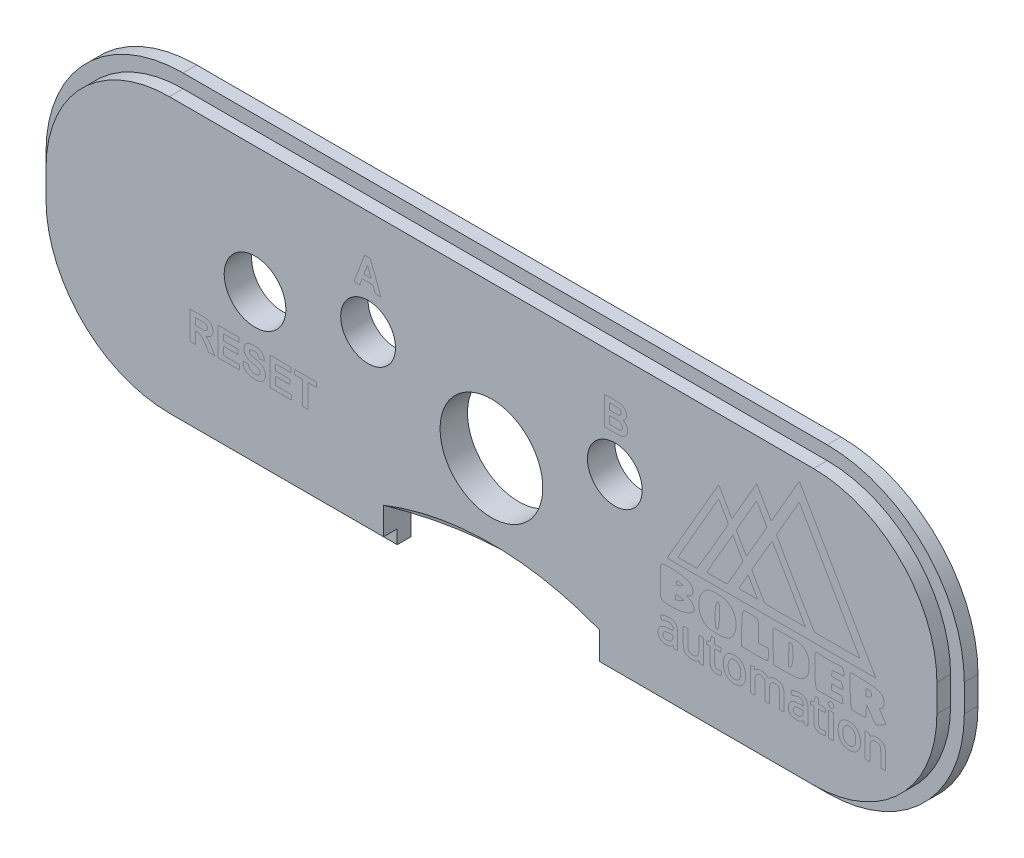
SolidWorks part; units mm, degrees
ref_plane "Front Plane" through (0, 0, 0) normal (0, 0, 1) x (1, 0, 0)
ref_plane "Top Plane" through (0, 0, 0) normal (0, 1, 0) x (1, 0, 0)
ref_plane "Right Plane" through (0, 0, 0) normal (1, 0, 0) x (0, 0, -1)
sketch "Sketch1" plane through (0, 0, 0) normal (0, 0, 1) x (1, 0, 0)
  line L1 (-33.5, -11) -> (33.5, -11)
  line L2 (-33.5, -11) -> (-33.5, 11)
  line L3 (-33.5, 11) -> (33.5, 11)
  line L4 (33.5, -11) -> (33.5, 11)
  line L5 (-33.5, -11) -> (33.5, 11) construction
  line L6 (-33.5, 11) -> (33.5, -11) construction
  point P0 (0, 0)
  dimension "D1" = 67
  dimension "D2" = 22
extrude "Boss-Extrude1" add sketch "Sketch1" along normal blind 1 contours L3 L4 L1 L2
fillet "Fillet1" radius 10 4 edges at (33.5, 11, 0.5) (33.5, -11, 0.5) (-33.5, -11, 0.5) (-33.5, 11, 0.5)
sketch "Sketch2" plane through (0, 0, 1) normal (0, 0, 1) x (1, 0, 0)
  line L8 (32.5, -1) -> (32.5, 1)
  line L9 (23.5, 10) -> (-23.5, 10)
  line L10 (-32.5, 1) -> (-32.5, -1)
  line L11 (-23.5, -10) -> (23.5, -10)
  line L12 (32.5, -1) -> (32.5, 1)
  line L13 (23.5, 10) -> (-23.5, 10)
  line L14 (-32.5, 1) -> (-32.5, -1)
  line L15 (-23.5, -10) -> (23.5, -10)
  arc A8 (32.5, 1) -> (23.5, 10) centre (23.5, 1) ccw
  arc A9 (-23.5, 10) -> (-32.5, 1) centre (-23.5, 1) ccw
  arc A10 (-32.5, -1) -> (-23.5, -10) centre (-23.5, -1) ccw
  arc A11 (23.5, -10) -> (32.5, -1) centre (23.5, -1) ccw
  arc A12 (32.5, 1) -> (23.5, 10) centre (23.5, 1) ccw
  arc A13 (-23.5, 10) -> (-32.5, 1) centre (-23.5, 1) ccw
  arc A14 (-32.5, -1) -> (-23.5, -10) centre (-23.5, -1) ccw
  arc A15 (23.5, -10) -> (32.5, -1) centre (23.5, -1) ccw
  dimension "D1" = 1
extrude "Boss-Extrude2" add sketch "Sketch2" along normal blind 1
sketch "Sketch3" plane through (0, 0, 0) normal (0, 0, -1) x (-1, 0, 0)
  line L0 (0, 0) -> (0, -11) construction
  line L1 (23.5, -11) -> (-23.5, -11) construction
  line L2 (-7.875, -14) -> (-7.875, -8)
  line L3 (-7.875, -14) -> (7.875, -14)
  line L4 (-7.875, -8) -> (7.875, -8)
  line L5 (7.875, -14) -> (7.875, -8)
  line L6 (-7.875, -14) -> (7.875, -8) construction
  line L7 (-7.875, -8) -> (7.875, -14) construction
  line L8 (23.5, -11) -> (-23.5, -11) construction
  dimension "D1" = 15.75
  dimension "D2" = 6
  dimension "D3" = 90
extrude "Cut-Extrude1" cut sketch "Sketch3" against normal through all
sketch "Sketch109" plane through (0, 0, 2) normal (0, 0, 1) x (1, 0, 0)
  line L0 (7.875, -8) -> (-7.875, -8) construction
  arc A0 (-7.875, -8) -> (7.875, -8) centre (0, -27.9219) cw
  point P3 (0, -6.5)
  dimension "D1" = 1.5
revolve "Cut-Revolve3" cut sketch "Sketch109" angle 360 about axis through (7.875, -8, 2) along (1, 0, 0) region at (0, -7.3982, 2)
sketch "Sketch112" plane through (0, 0, 0) normal (0, 0, -1) x (-1, 0, 0)
  line L0 (0, 0) -> (0, -11) construction
  line L1 (0, 0) -> (33.5, 0) construction
  line L2 (33.5, -1) -> (33.5, 1) construction
  line L3 (9, 0) -> (9, 2.38) construction
  line L4 (0, 0) -> (0, 11) construction
  line L5 (23.5, 11) -> (-23.5, 11) construction
  line L6 (0, 0) -> (-33.5, 0) construction
  line L7 (-33.5, -1) -> (-33.5, 1) construction
  line L9 (17.25, 0) -> (17.25, 0.8) construction
  circle A0 centre (0, -1.1) radius 3.75
  circle A1 centre (9, 2.38) radius 2
  circle A2 centre (-9, 2.38) radius 2
  circle A4 centre (17.25, 0.8) radius 2.25
  dimension "D2" = 7.5
  dimension "D5" = 4
  dimension "D11" = 4.5
  dimension "D1" = 1.1
  dimension "D3" = 2.38
  dimension "D4" = 9
  dimension "D9" = 0.8
  dimension "D10" = 17.25
extrude "Cut-Extrude2" cut sketch "Sketch112" against normal through all
sketch "Sketch113" plane through (0, 0, 2) normal (0, 0, 1) x (1, 0, 0)
  circle B0 centre (24.7803, -4.3035) radius 0.2103
  arc B1 (23.0498, 7.6782) -> (22.4641, 8.6806) centre (-50.9258, -34.8776) ccw
  arc B2 (22.4641, 8.6806) -> (22.314, 8.4273) centre (27.1246, 5.7481) ccw
  arc B3 (22.314, 8.4273) -> (21.9419, 7.7803) centre (222.0938, -106.9099) ccw
  arc B4 (20.9079, 5.9825) -> (21.9419, 7.7803) centre (-602.4956, 365.7341) ccw
  arc B5 (20.4342, 5.1705) -> (20.9079, 5.9825) centre (-80.1922, 64.4048) ccw
  arc B6 (20.4279, 5.1648) -> (20.4342, 5.1705) centre (20.4211, 5.1787) ccw
  arc B7 (20.4085, 5.162) -> (20.4279, 5.1648) centre (20.4139, 5.1931) ccw
  arc B8 (20.3929, 5.1705) -> (20.4085, 5.162) centre (20.4111, 5.1852) ccw
  arc B9 (20.1485, 5.5856) -> (20.3929, 5.1705) centre (46.8153, 21.0091) ccw
  arc B10 (19.8754, 6.0603) -> (20.1485, 5.5856) centre (97.988, 50.6909) ccw
  arc B11 (19.8754, 6.0603) -> (19.4298, 6.8395) centre (-513.4407, -298.3467) ccw
  arc B12 (19.4298, 6.8395) -> (19.3508, 6.9696) centre (18.1163, 6.1313) ccw
  arc B13 (19.3508, 6.9696) -> (19.2181, 6.7469) centre (22.9527, 4.672) ccw
  arc B14 (19.2181, 6.7469) -> (18.8904, 6.178) centre (165.0061, -77.6169) ccw
  arc B15 (17.9807, 4.5971) -> (18.8904, 6.178) centre (-631.1168, 379.1333) ccw
  arc B16 (17.5642, 3.8828) -> (17.9807, 4.5971) centre (-73.0363, 57.1929) ccw
  arc B17 (17.559, 3.8782) -> (17.5642, 3.8828) centre (17.5534, 3.8896) ccw
  arc B18 (17.5303, 3.8828) -> (17.559, 3.8782) centre (17.5479, 3.9004) ccw
  arc B19 (17.3436, 4.2026) -> (17.5303, 3.8828) centre (36.9073, 15.4072) ccw
  arc B20 (16.9792, 4.8473) -> (17.3436, 4.2026) centre (83.5983, 42.0848) ccw
  arc B21 (16.9792, 4.8473) -> (16.608, 5.488) centre (-8.8306, -9.6775) ccw
  arc B22 (16.608, 5.488) -> (16.6012, 5.494) centre (16.5938, 5.4789) ccw
  arc B23 (16.6012, 5.494) -> (16.5804, 5.4971) centre (16.5861, 5.4635) ccw
  arc B24 (16.5804, 5.4971) -> (16.5639, 5.488) centre (16.583, 5.4728) ccw
  arc B25 (16.5639, 5.488) -> (15.6903, 3.9876) centre (563.2563, -313.8159) ccw
  arc B26 (15.6903, 3.9876) -> (13.0854, -0.5227) centre (988.6695, -560.9533) ccw
  arc B27 (13.0854, -0.5227) -> (12.8193, -0.9943) centre (28.6752, -9.63) ccw
  arc B28 (12.8193, -0.9943) -> (14.4045, -0.9969) centre (13.8688, 157.752) ccw
  arc B29 (14.4045, -0.9969) -> (26.458, -0.9759) centre (11.1994, 5300.4417) ccw
  arc B30 (26.458, -0.9759) -> (28.0431, -0.9678) centre (26.4404, 157.9147) ccw
  arc B31 (28.0431, -0.9678) -> (27.4665, 0.0399) centre (-46.3137, -42.8404) ccw
  arc B32 (27.4665, 0.0399) -> (23.0498, 7.6782) centre (-2435.592, -1419.0663) ccw
  arc B33 (22.4588, 7.3225) -> (22.4427, 7.3136) centre (22.4614, 7.2987) ccw
  arc B34 (22.4427, 7.3136) -> (21.2219, 5.2134) centre (242.6481, -122.0921) ccw
  arc B35 (21.2219, 5.2134) -> (20.9228, 4.6838) centre (57.5521, -15.6522) ccw
  arc B36 (20.9228, 4.6838) -> (20.806, 4.4561) centre (22.5174, 3.7223) ccw
  arc B37 (20.806, 4.4561) -> (21.0886, 3.9431) centre (29.0248, 8.6476) ccw
  arc B38 (21.0886, 3.9431) -> (21.7639, 2.7668) centre (193.5014, 102.1518) ccw
  arc B39 (21.7639, 2.7668) -> (22.574, 1.3717) centre (359.7991, 198.1317) ccw
  arc B40 (22.574, 1.3717) -> (23.2609, 0.2021) centre (193.9122, 101.2111) ccw
  arc B41 (23.2609, 0.2021) -> (23.5665, -0.2976) centre (31.2761, 4.7607) ccw
  arc B42 (23.5665, -0.2976) -> (23.928, -0.3093) centre (23.8658, 3.3467) ccw
  arc B43 (23.928, -0.3093) -> (24.7484, -0.3128) centre (24.6753, 79.558) ccw
  arc B44 (24.7484, -0.3128) -> (26.5287, -0.3045) centre (24.7463, 191.7103) ccw
  arc B45 (26.5287, -0.3045) -> (26.8701, -0.2976) centre (26.5497, 7.0805) ccw
  arc B46 (26.8701, -0.2976) -> (26.5579, 0.2553) centre (5.1072, -12.2228) ccw
  arc B47 (26.5579, 0.2553) -> (25.7535, 1.6575) centre (-530.4511, -318.3624) ccw
  arc B48 (25.7535, 1.6575) -> (22.4855, 7.3136) centre (-1374.7342, -803.7385) ccw
  arc B49 (22.4855, 7.3136) -> (22.479, 7.3195) centre (22.4719, 7.3052) ccw
  arc B50 (22.479, 7.3195) -> (22.4588, 7.3225) centre (22.4644, 7.2902) ccw
  arc B51 (19.3455, 5.8495) -> (19.3295, 5.8408) centre (19.348, 5.8259) ccw
  arc B52 (19.3295, 5.8408) -> (18.7398, 4.8406) centre (147.9054, -70.6335) ccw
  arc B53 (18.7398, 4.8406) -> (17.878, 3.3272) centre (88.5187, -35.8996) ccw
  arc B54 (17.878, 3.3272) -> (17.8735, 3.3121) centre (17.9108, 3.3093) ccw
  arc B55 (17.8735, 3.3121) -> (17.8799, 3.2792) centre (17.9407, 3.3081) ccw
  arc B56 (17.8799, 3.2792) -> (17.8956, 3.2478) centre (18.1036, 3.3715) ccw
  arc B57 (17.8956, 3.2478) -> (18.1652, 2.768) centre (72.8714, 33.8162) ccw
  arc B58 (18.1652, 2.768) -> (18.5849, 2.0572) centre (39.8931, 15.1199) ccw
  arc B59 (18.5849, 2.0572) -> (18.5921, 2.0509) centre (18.6, 2.0671) ccw
  arc B60 (18.5921, 2.0509) -> (18.6139, 2.0477) centre (18.608, 2.0832) ccw
  arc B61 (18.6139, 2.0477) -> (18.6314, 2.0572) centre (18.6112, 2.0734) ccw
  arc B62 (18.6314, 2.0572) -> (18.9279, 2.5563) centre (-146.4854, 100.496) ccw
  arc B63 (18.9279, 2.5563) -> (19.5138, 3.5588) centre (-66.4571, 53.1324) ccw
  arc B64 (19.5138, 3.5588) -> (20.0829, 4.5708) centre (-30.3015, 32.237) ccw
  arc B65 (20.0829, 4.5708) -> (20.0842, 4.6057) centre (20.0467, 4.5897) ccw
  arc B66 (20.0842, 4.6057) -> (20.0764, 4.6241) centre (19.9691, 4.5677) ccw
  arc B67 (20.0764, 4.6241) -> (20.0564, 4.659) centre (19.5515, 4.3456) ccw
  arc B68 (20.0564, 4.659) -> (19.7882, 5.1349) centre (-49.054, -33.97) ccw
  arc B69 (19.7882, 5.1349) -> (19.3722, 5.8408) centre (-3.5376, -8.1372) ccw
  arc B70 (19.3722, 5.8408) -> (19.3656, 5.8466) centre (19.3583, 5.8317) ccw
  arc B71 (19.3656, 5.8466) -> (19.3455, 5.8495) centre (19.351, 5.8169) ccw
  arc B72 (16.5809, 4.597) -> (16.5652, 4.5884) centre (16.5834, 4.574) ccw
  arc B73 (16.5652, 4.5884) -> (15.8757, 3.4009) centre (385.0113, -210.1417) ccw
  arc B74 (15.8757, 3.4009) -> (13.8222, -0.1701) centre (651.1096, -364.262) ccw
  arc B75 (13.8222, -0.1701) -> (13.6131, -0.5445) centre (23.6461, -5.902) ccw
  arc B76 (13.6131, -0.5445) -> (13.7546, -0.5514) centre (13.7475, 0.7526) ccw
  arc B77 (13.7546, -0.5514) -> (14.4889, -0.5597) centre (14.4474, 28.3545) ccw
  arc B78 (14.4889, -0.5597) -> (14.8325, -0.5563) centre (14.5181, 13.5964) ccw
  arc B79 (14.8325, -0.5563) -> (14.994, -0.5445) centre (14.8532, 0.2758) ccw
  arc B80 (14.994, -0.5445) -> (15.2501, -0.1302) centre (9.6282, 3.0577) ccw
  arc B81 (15.2501, -0.1302) -> (15.8188, 0.8358) centre (-101.2446, 69.1044) ccw
  arc B82 (15.8188, 0.8358) -> (16.4879, 1.988) centre (-213.4808, 134.769) ccw
  arc B83 (16.4879, 1.988) -> (17.0452, 2.9609) centre (-100.4773, 69.6297) ccw
  arc B84 (17.0452, 2.9609) -> (17.2783, 3.389) centre (11.5032, 6.2562) ccw
  arc B85 (17.2783, 3.389) -> (17.2311, 3.4975) centre (16.8233, 3.2558) ccw
  arc B86 (17.2311, 3.4975) -> (17.1096, 3.7221) centre (10.5956, 0.0519) ccw
  arc B87 (17.1096, 3.7221) -> (16.9445, 4.0123) centre (-4.7311, -8.5085) ccw
  arc B88 (16.9445, 4.0123) -> (16.6069, 4.5884) centre (-26.7767, -21.22) ccw
  arc B89 (16.6069, 4.5884) -> (16.6005, 4.5941) centre (16.5936, 4.5799) ccw
  arc B90 (16.6005, 4.5941) -> (16.5809, 4.597) centre (16.5863, 4.5654) ccw
  arc B91 (20.4759, 3.8925) -> (20.4584, 3.8828) centre (20.4788, 3.8664) ccw
  arc B92 (20.4584, 3.8828) -> (19.871, 2.8814) centre (94.2003, -40.0406) ccw
  arc B93 (19.871, 2.8814) -> (19.0069, 1.3693) centre (174.5101, -86.4937) ccw
  arc B94 (19.0069, 1.3693) -> (19.0069, 1.3252) centre (19.0468, 1.3473) ccw
  arc B95 (19.2208, 0.95) -> (19.0069, 1.3252) centre (-322.3255, -193.495) ccw
  arc B96 (19.2208, 0.95) -> (19.6927, 0.1288) centre (112.6319, 54.0895) ccw
  arc B97 (19.6927, 0.1288) -> (19.8715, -0.1704) centre (32.0786, 7.3272) ccw
  arc B98 (19.8715, -0.1704) -> (19.9594, -0.2976) centre (20.5255, 0.1875) ccw
  arc B99 (19.9594, -0.2976) -> (20.2834, -0.3093) centre (20.2289, 2.6582) ccw
  arc B100 (20.2834, -0.3093) -> (21.0141, -0.3128) centre (20.9488, 62.9553) ccw
  arc B101 (21.0141, -0.3128) -> (22.5976, -0.3045) centre (21.011, 151.3463) ccw
  arc B102 (22.5976, -0.3045) -> (22.9013, -0.2976) centre (22.6157, 5.5588) ccw
  arc B103 (22.9013, -0.2976) -> (22.7323, 0.0083) centre (16.1932, -3.8033) ccw
  arc B104 (22.7323, 0.0083) -> (22.2939, 0.7793) centre (-142.6654, -93.5283) ccw
  arc B105 (22.2939, 0.7793) -> (20.5049, 3.8828) centre (-368.428, -222.3883) ccw
  arc B106 (20.5049, 3.8828) -> (20.4978, 3.8893) centre (20.4901, 3.8737) ccw
  arc B107 (20.4978, 3.8893) -> (20.4759, 3.8925) centre (20.482, 3.8575) ccw
  arc B108 (17.6618, 2.7554) -> (17.6055, 2.8413) centre (17.0631, 2.4241) ccw
  arc B109 (17.6055, 2.8413) -> (17.403, 2.5012) centre (26.1163, -2.4553) ccw
  arc B110 (17.403, 2.5012) -> (15.9054, -0.0933) centre (300.8898, -162.8679) ccw
  arc B111 (15.9054, -0.0933) -> (15.7121, -0.4387) centre (24.5344, -5.1476) ccw
  arc B112 (15.7121, -0.4387) -> (15.8635, -0.4456) centre (15.8557, 1.0428) ccw
  arc B113 (15.8635, -0.4456) -> (16.65, -0.4539) centre (16.6054, 32.7305) ccw
  arc B114 (16.65, -0.4539) -> (17.0173, -0.4504) centre (16.6812, 15.719) ccw
  arc B115 (17.0173, -0.4504) -> (17.1887, -0.4387) centre (17.0401, 0.4741) ccw
  arc B116 (17.1887, -0.4387) -> (17.2918, -0.2862) centre (16.3924, 0.2107) ccw
  arc B117 (17.2918, -0.2862) -> (17.5092, 0.0781) centre (1.0663, 9.6436) ccw
  arc B118 (17.5092, 0.0781) -> (18.3366, 1.5457) centre (-30.7808, 28.2709) ccw
  arc B119 (18.3366, 1.5457) -> (18.3415, 1.5643) centre (18.2995, 1.5655) ccw
  arc B120 (18.3415, 1.5643) -> (18.3312, 1.6044) centre (18.2613, 1.565) ccw
  arc B121 (18.3312, 1.6044) -> (18.3101, 1.6427) centre (17.9362, 1.4125) ccw
  arc B122 (18.3101, 1.6427) -> (17.6618, 2.7554) centre (-25.6685, -23.2378) ccw
  arc B123 (18.81, 0.7616) -> (18.7344, 0.8833) centre (17.6322, 0.1141) ccw
  arc B124 (18.7344, 0.8833) -> (18.6576, 0.7616) centre (19.84, 0.1009) ccw
  arc B125 (18.6576, 0.7616) -> (18.1168, -0.1705) centre (55.0739, -20.9883) ccw
  arc B126 (18.1168, -0.1705) -> (18.0493, -0.2976) centre (19.2775, -0.8691) ccw
  arc B127 (18.0493, -0.2976) -> (18.1925, -0.3029) centre (18.1707, 1.0404) ccw
  arc B128 (18.1925, -0.3029) -> (19.2654, -0.3029) centre (18.7287, 41.7799) ccw
  arc B129 (19.2654, -0.3029) -> (19.4087, -0.2976) centre (19.2872, 1.0437) ccw
  arc B130 (19.4087, -0.2976) -> (19.3422, -0.1705) centre (18.1829, -0.8575) ccw
  arc B131 (19.3422, -0.1705) -> (18.81, 0.7616) centre (-17.5144, -20.5975) ccw
  arc B132 (16.5486, -1.4301) -> (16.0876, -1.4353) centre (16.3743, -6.4364) ccw
  arc B133 (16.0876, -1.4353) -> (16.0367, -1.4411) centre (16.1112, -1.8709) ccw
  arc B134 (16.0367, -1.4411) -> (15.9369, -1.4676) centre (16.1406, -2.0333) ccw
  arc B135 (15.9369, -1.4676) -> (15.7472, -1.5503) centre (16.4093, -2.8091) ccw
  arc B136 (15.7472, -1.5503) -> (15.6202, -1.6381) centre (16.0494, -2.1232) ccw
  arc B137 (15.6202, -1.6381) -> (15.5576, -1.6996) centre (16.7343, -2.8354) ccw
  arc B138 (15.5576, -1.6996) -> (15.338, -1.9733) centre (16.9564, -3.0471) ccw
  arc B139 (15.338, -1.9733) -> (15.2803, -2.0748) centre (15.9772, -2.4033) ccw
  arc B140 (15.2803, -2.0748) -> (15.2145, -2.2379) centre (16.5861, -2.6968) ccw
  arc B141 (15.2145, -2.2379) -> (15.144, -2.5201) centre (16.6587, -2.7488) ccw
  arc B142 (15.144, -2.5201) -> (15.2498, -3.3491) centre (16.6176, -2.7532) ccw
  arc B143 (15.2498, -3.3491) -> (15.3866, -3.5876) centre (16.3259, -2.8904) ccw
  arc B144 (15.3866, -3.5876) -> (15.5144, -3.7195) centre (15.9962, -3.1249) ccw
  arc B145 (15.5144, -3.7195) -> (15.559, -3.7543) centre (17.4776, -1.2454) ccw
  arc B146 (15.559, -3.7543) -> (15.652, -3.8191) centre (16.3083, -2.7781) ccw
  arc B147 (15.652, -3.8191) -> (15.8191, -3.8916) centre (15.9822, -3.2867) ccw
  arc B148 (15.8191, -3.8916) -> (16.0265, -3.9321) centre (16.1609, -2.6946) ccw
  arc B149 (16.0265, -3.9321) -> (16.3078, -3.9544) centre (16.4156, -0.8066) ccw
  arc B150 (16.3078, -3.9544) -> (16.6859, -3.9563) centre (16.5253, 1.7828) ccw
  arc B151 (16.6859, -3.9563) -> (16.9255, -3.9312) centre (16.6295, -2.262) ccw
  arc B152 (16.9255, -3.9312) -> (17.2254, -3.843) centre (16.6243, -2.3532) ccw
  arc B153 (17.2254, -3.843) -> (17.4017, -3.7372) centre (16.9716, -3.2201) ccw
  arc B154 (17.4017, -3.7372) -> (17.5303, -3.6164) centre (16.4457, -2.5904) ccw
  arc B155 (17.5303, -3.6164) -> (17.6694, -3.4207) centre (16.8541, -2.9884) ccw
  arc B156 (17.6694, -3.4207) -> (17.7667, -3.1919) centre (16.4829, -2.7811) ccw
  arc B157 (17.7667, -3.1919) -> (17.8329, -2.8891) centre (16.1896, -2.6884) ccw
  arc B158 (17.8329, -2.8891) -> (17.8353, -2.5388) centre (16.3148, -2.7038) ccw
  arc B159 (17.8353, -2.5388) -> (17.7961, -2.2965) centre (16.2196, -2.6759) ccw
  arc B160 (17.7961, -2.2965) -> (17.7281, -2.1144) centre (16.7108, -2.598) ccw
  arc B161 (17.7281, -2.1144) -> (17.6222, -1.9292) centre (16.754, -2.5481) ccw
  arc B162 (17.6222, -1.9292) -> (17.4188, -1.7118) centre (16.6162, -2.6666) ccw
  arc B163 (17.4188, -1.7118) -> (17.3267, -1.6325) centre (16.2641, -2.9595) ccw
  arc B164 (17.3267, -1.6325) -> (17.2254, -1.5676) centre (16.9399, -2.1252) ccw
  arc B165 (17.2254, -1.5676) -> (17.0819, -1.5068) centre (16.6322, -2.7691) ccw
  arc B166 (17.0819, -1.5068) -> (16.8549, -1.4529) centre (16.7201, -2.5248) ccw
  arc B167 (16.8549, -1.4529) -> (16.5486, -1.4301) centre (16.4215, -5.2042) ccw
  arc B168 (13.5371, -1.5141) -> (13.3183, -1.497) centre (13.0762, -6.0045) ccw
  arc B169 (13.3183, -1.497) -> (13.0559, -1.4905) centre (12.9776, -9.9234) ccw
  arc B170 (13.0559, -1.4905) -> (12.688, -1.502) centre (13.0154, -6.0778) ccw
  arc B171 (12.688, -1.502) -> (12.5158, -1.5235) centre (12.8283, -3.33) ccw
  arc B172 (12.5158, -1.5235) -> (12.4299, -1.5633) centre (12.5529, -1.7159) ccw
  arc B173 (12.4299, -1.5633) -> (12.3394, -1.6734) centre (12.617, -1.8094) ccw
  arc B174 (12.3394, -1.6734) -> (12.3254, -1.7449) centre (12.5721, -1.756) ccw
  arc B175 (12.3254, -1.7449) -> (12.3194, -1.8664) centre (14.0508, -1.8919) ccw
  arc B176 (12.3194, -1.8664) -> (12.3202, -2.1741) centre (20.0405, -1.9994) ccw
  arc B177 (12.323, -2.5748) -> (12.3202, -2.1741) centre (-15.8258, -2.5727) ccw
  arc B178 (12.323, -2.5748) -> (12.3294, -3.0901) centre (48.6349, -2.3817) ccw
  arc B179 (12.3294, -3.0901) -> (12.3482, -3.6049) centre (28.8759, -2.7439) ccw
  arc B180 (12.3482, -3.6049) -> (12.3565, -3.6802) centre (12.9717, -3.5745) ccw
  arc B181 (12.3565, -3.6802) -> (12.3802, -3.7512) centre (12.614, -3.6335) ccw
  arc B182 (12.3802, -3.7512) -> (12.4284, -3.8044) centre (12.5076, -3.6841) ccw
  arc B183 (12.4284, -3.8044) -> (12.4962, -3.8328) centre (12.5505, -3.6086) ccw
  arc B184 (12.4962, -3.8328) -> (12.5687, -3.8518) centre (13.2941, -0.9357) ccw
  arc B185 (12.5687, -3.8518) -> (12.7715, -3.8871) centre (12.835, -2.9214) ccw
  arc B186 (12.7715, -3.8871) -> (12.9831, -3.8974) centre (13.2923, 4.6179) ccw
  arc B187 (12.9831, -3.8974) -> (13.3007, -3.8959) centre (13.123, 0.1163) ccw
  arc B188 (13.3007, -3.8959) -> (13.567, -3.8805) centre (12.529, 11.787) ccw
  arc B189 (13.567, -3.8805) -> (13.8317, -3.8508) centre (13.3319, -0.5931) ccw
  arc B190 (13.8317, -3.8508) -> (14.0853, -3.7917) centre (13.5443, -2.0442) ccw
  arc B191 (14.0853, -3.7917) -> (14.4435, -3.6536) centre (13.2529, -1.0986) ccw
  arc B192 (14.4435, -3.6536) -> (14.5768, -3.5722) centre (14.1527, -3.0279) ccw
  arc B193 (14.5768, -3.5722) -> (14.6982, -3.4659) centre (13.8578, -2.6287) ccw
  arc B194 (14.6982, -3.4659) -> (14.7454, -3.4126) centre (14.2687, -3.0381) ccw
  arc B195 (14.7454, -3.4126) -> (14.7735, -3.3667) centre (14.5861, -3.2831) ccw
  arc B196 (14.7735, -3.3667) -> (14.7842, -3.325) centre (14.613, -3.3034) ccw
  arc B197 (14.7842, -3.325) -> (14.7814, -3.2358) centre (14.4897, -3.2898) ccw
  arc B198 (14.7814, -3.2358) -> (14.7647, -3.1463) centre (13.1551, -3.4919) ccw
  arc B199 (14.7647, -3.1463) -> (14.6601, -2.9252) centre (14.2905, -3.2354) ccw
  arc B200 (14.6601, -2.9252) -> (14.5795, -2.8464) centre (14.3385, -3.1735) ccw
  arc B201 (14.5795, -2.8464) -> (14.5219, -2.8117) centre (14.2727, -3.2906) ccw
  arc B202 (14.5219, -2.8117) -> (14.4609, -2.7824) centre (14.0283, -3.7602) ccw
  arc B203 (14.4609, -2.7824) -> (14.3989, -2.755) centre (4.4041, -25.5071) ccw
  arc B204 (14.3377, -2.726) -> (14.3989, -2.755) centre (14.8709, -1.6802) ccw
  arc B205 (14.2797, -2.6919) -> (14.3377, -2.726) centre (14.5948, -2.2218) ccw
  arc B206 (14.2732, -2.6842) -> (14.2797, -2.6919) centre (14.2913, -2.6756) ccw
  arc B207 (14.27, -2.6617) -> (14.2732, -2.6842) centre (14.3073, -2.6679) ccw
  arc B208 (14.2797, -2.6432) -> (14.27, -2.6617) centre (14.2986, -2.6649) ccw
  arc B209 (14.3253, -2.617) -> (14.2797, -2.6432) centre (14.4813, -2.9415) ccw
  arc B210 (14.3739, -2.5958) -> (14.3253, -2.617) centre (14.6421, -3.2761) ccw
  arc B211 (14.4235, -2.5762) -> (14.3739, -2.5958) centre (69.7908, -143.1383) ccw
  arc B212 (14.4235, -2.5762) -> (14.4721, -2.5551) centre (14.1528, -1.8888) ccw
  arc B213 (14.4721, -2.5551) -> (14.5725, -2.4817) centre (14.3283, -2.2528) ccw
  arc B214 (14.5725, -2.4817) -> (14.6413, -2.3966) centre (14.0572, -1.995) ccw
  arc B215 (14.6413, -2.3966) -> (14.6647, -2.3602) centre (14.3588, -2.1888) ccw
  arc B216 (14.6647, -2.3602) -> (14.6854, -2.2996) centre (14.5077, -2.2729) ccw
  arc B217 (14.6854, -2.2996) -> (14.6947, -2.1795) centre (12.9737, -2.1064) ccw
  arc B218 (14.6947, -2.1795) -> (14.6854, -1.9997) centre (13.7136, -2.1402) ccw
  arc B219 (14.6854, -1.9997) -> (14.6777, -1.9692) centre (14.499, -2.0301) ccw
  arc B220 (14.6777, -1.9692) -> (14.6503, -1.9119) centre (14.4139, -2.0602) ccw
  arc B221 (14.6503, -1.9119) -> (14.6148, -1.8586) centre (13.995, -2.3101) ccw
  arc B222 (14.6148, -1.8586) -> (14.5178, -1.7616) centre (14.286, -2.0904) ccw
  arc B223 (14.5178, -1.7616) -> (14.4503, -1.717) centre (13.8398, -2.7128) ccw
  arc B224 (14.4503, -1.717) -> (14.3414, -1.6646) centre (14.1322, -2.2392) ccw
  arc B225 (14.3414, -1.6646) -> (13.9533, -1.5676) centre (13.5828, -3.8742) ccw
  arc B226 (13.9533, -1.5676) -> (13.5371, -1.5141) centre (12.9153, -8.0023) ccw
  arc B227 (18.6217, -1.4925) -> (18.4336, -1.5058) centre (18.702, -3.9603) ccw
  arc B228 (18.4336, -1.5058) -> (18.4056, -1.517) centre (18.4401, -1.563) ccw
  arc B229 (18.4056, -1.517) -> (18.3841, -1.5403) centre (18.4616, -1.5904) ccw
  arc B230 (18.3841, -1.5403) -> (18.3677, -1.5713) centre (18.5415, -1.6433) ccw
  arc B231 (18.3677, -1.5713) -> (18.3552, -1.6054) centre (18.7265, -1.7217) ccw
  arc B232 (18.3552, -1.6054) -> (18.3149, -1.7775) centre (19.4863, -1.9612) ccw
  arc B233 (18.3149, -1.7775) -> (18.2925, -1.9909) centre (20.4574, -2.1102) ccw
  arc B234 (18.2925, -1.9909) -> (18.2519, -3.7855) centre (36.6022, -3.3029) ccw
  arc B235 (18.2519, -3.7855) -> (18.2573, -3.8517) centre (18.5874, -3.7914) ccw
  arc B236 (18.2573, -3.8517) -> (18.3718, -3.8582) centre (18.368, -2.916) ccw
  arc B237 (18.3718, -3.8582) -> (18.6546, -3.8645) centre (18.9767, 16.9509) ccw
  arc B238 (18.6546, -3.8645) -> (19.7918, -3.8695) centre (19.4232, 42.266) ccw
  arc B239 (19.7918, -3.8695) -> (20.1005, -3.8254) centre (19.7736, -2.6396) ccw
  arc B240 (20.1005, -3.8254) -> (20.1594, -3.7972) centre (20.0548, -3.654) ccw
  arc B241 (20.1594, -3.7972) -> (20.1799, -3.7636) centre (20.1242, -3.7527) ccw
  arc B242 (20.1799, -3.7636) -> (20.1938, -3.6214) centre (17.4074, -3.4193) ccw
  arc B243 (20.1938, -3.6214) -> (20.2034, -3.3355) centre (16.4576, -3.3535) ccw
  arc B244 (20.2034, -3.3355) -> (20.1975, -3.0492) centre (12.6779, -3.3471) ccw
  arc B245 (20.1975, -3.0492) -> (20.1946, -3.0368) centre (20.1616, -3.0509) ccw
  arc B246 (20.1946, -3.0368) -> (20.1534, -3.0051) centre (20.146, -3.0575) ccw
  arc B247 (20.1534, -3.0051) -> (20.0282, -3.0049) centre (20.087, -4.8247) ccw
  arc B248 (20.0282, -3.0049) -> (19.9029, -3.011) centre (20.1513, -6.8136) ccw
  arc B249 (19.7776, -3.019) -> (19.9029, -3.011) centre (16.9214, 42.6455) ccw
  arc B250 (19.6524, -3.0244) -> (19.7776, -3.019) centre (19.574, 0.2354) ccw
  arc B251 (19.5272, -3.0228) -> (19.6524, -3.0244) centre (19.6119, -1.341) ccw
  arc B252 (19.506, -3.0098) -> (19.5272, -3.0228) centre (19.5294, -2.9954) ccw
  arc B253 (19.4919, -2.9699) -> (19.506, -3.0098) centre (19.5643, -2.9669) ccw
  arc B254 (19.4831, -2.6894) -> (19.4919, -2.9699) centre (28.5511, -2.5447) ccw
  arc B255 (19.4804, -2.4087) -> (19.4831, -2.6894) centre (42.1277, -2.3279) ccw
  arc B256 (19.4804, -2.4087) -> (19.4785, -2.128) centre (-26.4071, -2.5726) ccw
  arc B257 (19.4785, -2.128) -> (19.4724, -1.8476) centre (8.101, -2.2382) ccw
  arc B258 (19.4724, -1.8476) -> (19.4567, -1.5676) centre (12.9871, -2.0704) ccw
  arc B259 (19.4567, -1.5676) -> (19.4504, -1.5516) centre (19.4268, -1.5701) ccw
  arc B260 (19.4504, -1.5516) -> (19.4364, -1.5395) centre (19.4117, -1.5824) ccw
  arc B261 (19.4364, -1.5395) -> (19.4176, -1.5311) centre (19.3882, -1.6217) ccw
  arc B262 (19.4176, -1.5311) -> (19.3773, -1.5235) centre (19.3684, -1.6811) ccw
  arc B263 (19.1886, -1.511) -> (19.3773, -1.5235) centre (20.9022, 23.0329) ccw
  arc B264 (19.1886, -1.511) -> (18.9995, -1.4991) centre (18.1817, -15.9343) ccw
  arc B265 (18.9995, -1.4991) -> (18.8104, -1.4916) centre (18.6845, -7.0578) ccw
  arc B266 (18.8104, -1.4916) -> (18.6217, -1.4925) centre (18.7329, -4.9126) ccw
  arc B267 (25.1452, -1.5058) -> (25.241, -1.5021) centre (25.029, 2.7137) ccw
  arc B268 (25.3374, -1.4981) -> (25.241, -1.5021) centre (25.5182, -7.0188) ccw
  arc B269 (25.4335, -1.4977) -> (25.3374, -1.4981) centre (25.3918, -3.1532) ccw
  arc B270 (25.5284, -1.5049) -> (25.4335, -1.4977) centre (25.4097, -2.4467) ccw
  arc B271 (25.6215, -1.5235) -> (25.5284, -1.5049) centre (25.4452, -2.1641) ccw
  arc B272 (25.6446, -1.5378) -> (25.6215, -1.5235) centre (25.6084, -1.5705) ccw
  arc B273 (25.6595, -1.5622) -> (25.6446, -1.5378) centre (25.5826, -1.5924) ccw
  arc B274 (25.6691, -1.5928) -> (25.6595, -1.5622) centre (25.4694, -1.6385) ccw
  arc B275 (25.676, -1.6253) -> (25.6691, -1.5928) centre (24.7347, -1.8098) ccw
  arc B276 (25.676, -1.6253) -> (25.6832, -1.6558) centre (26.0587, -1.5513) ccw
  arc B277 (25.7273, -1.8851) -> (25.6832, -1.6558) centre (24.492, -2.0037) ccw
  arc B278 (25.7296, -1.9761) -> (25.7273, -1.8851) centre (25.2539, -1.9424) ccw
  arc B279 (25.7256, -2.0011) -> (25.7296, -1.9761) centre (25.5859, -1.9663) ccw
  arc B280 (25.7179, -2.0169) -> (25.7256, -2.0011) centre (25.6911, -1.994) ccw
  arc B281 (25.655, -2.0252) -> (25.7179, -2.0169) centre (25.6581, -1.8064) ccw
  arc B282 (25.5097, -2.0319) -> (25.655, -2.0252) centre (25.3194, 3.716) ccw
  arc B283 (25.5097, -2.0319) -> (25.1135, -2.048) centre (26.0009, -18.9285) ccw
  arc B284 (25.1135, -2.048) -> (24.9335, -2.0615) centre (25.3154, -5.963) ccw
  arc B285 (24.9335, -2.0615) -> (24.8832, -2.0793) centre (24.9418, -2.1647) ccw
  arc B286 (24.8832, -2.0793) -> (24.863, -2.1056) centre (24.9079, -2.1192) ccw
  arc B287 (24.863, -2.1056) -> (24.8303, -2.3001) centre (25.8218, -2.3666) ccw
  arc B288 (24.8303, -2.3001) -> (24.8277, -2.4319) centre (26.277, -2.3946) ccw
  arc B289 (24.8277, -2.4319) -> (24.838, -2.4522) centre (24.8595, -2.4285) ccw
  arc B290 (24.838, -2.4522) -> (24.8718, -2.4672) centre (24.8752, -2.4138) ccw
  arc B291 (24.8718, -2.4672) -> (25.0834, -2.4655) centre (24.9571, 0.2169) ccw
  arc B292 (25.2952, -2.4573) -> (25.0834, -2.4655) centre (25.4192, -8.3929) ccw
  arc B293 (25.401, -2.4583) -> (25.2952, -2.4573) centre (25.3301, -4.3431) ccw
  arc B294 (25.4834, -2.4708) -> (25.401, -2.4583) centre (25.3966, -2.7666) ccw
  arc B295 (25.5333, -2.4936) -> (25.4834, -2.4708) centre (25.4345, -2.6434) ccw
  arc B296 (25.5611, -2.5235) -> (25.5333, -2.4936) centre (25.4743, -2.5765) ccw
  arc B297 (25.5862, -2.5818) -> (25.5611, -2.5235) centre (25.273, -2.6819) ccw
  arc B298 (25.6461, -2.7961) -> (25.5862, -2.5818) centre (22.7378, -3.4933) ccw
  arc B299 (25.6579, -2.8513) -> (25.6461, -2.7961) centre (24.6406, -3.041) ccw
  arc B300 (25.66, -2.8769) -> (25.6579, -2.8513) centre (25.5931, -2.8694) ccw
  arc B301 (25.6421, -2.8856) -> (25.66, -2.8769) centre (25.6316, -2.8414) ccw
  arc B302 (25.4949, -2.9194) -> (25.6421, -2.8856) centre (25.3134, -1.7924) ccw
  arc B303 (25.4451, -2.9258) -> (25.4949, -2.9194) centre (25.3861, -2.2617) ccw
  arc B304 (25.2052, -2.9334) -> (25.4451, -2.9258) centre (25.2161, 0.4849) ccw
  arc B305 (25.2052, -2.9334) -> (24.965, -2.9357) centre (25.1363, -8.3472) ccw
  arc B306 (24.965, -2.9357) -> (24.8454, -2.9434) centre (25.0325, -4.917) ccw
  arc B307 (24.8454, -2.9434) -> (24.8254, -2.9543) centre (24.851, -2.9773) ccw
  arc B308 (24.8254, -2.9543) -> (24.8101, -2.9875) centre (24.8687, -2.9945) ccw
  arc B309 (24.8101, -2.9875) -> (24.7963, -3.2595) centre (28.2105, -3.2957) ccw
  arc B310 (24.7963, -3.2595) -> (24.797, -3.3283) centre (26.2269, -3.28) ccw
  arc B311 (24.797, -3.3283) -> (24.8008, -3.3586) centre (24.8851, -3.3326) ccw
  arc B312 (24.8008, -3.3586) -> (24.8817, -3.3576) centre (24.8347, -2.8272) ccw
  arc B313 (25.2893, -3.3361) -> (24.8817, -3.3576) centre (53.4413, -542.2088) ccw
  arc B314 (25.478, -3.3283) -> (25.2893, -3.3361) centre (25.7113, -11.2794) ccw
  arc B315 (25.5647, -3.331) -> (25.478, -3.3283) centre (25.5105, -3.6886) ccw
  arc B316 (25.5783, -3.3595) -> (25.5647, -3.331) centre (25.5111, -3.374) ccw
  arc B317 (25.5927, -3.4169) -> (25.5783, -3.3595) centre (24.9418, -3.5504) ccw
  arc B318 (25.6303, -3.6401) -> (25.5927, -3.4169) centre (21.6718, -4.1912) ccw
  arc B319 (25.6303, -3.7989) -> (25.6303, -3.6401) centre (25.0726, -3.7195) ccw
  arc B320 (25.6112, -3.8237) -> (25.6303, -3.7989) centre (25.5977, -3.7935) ccw
  arc B321 (25.6038, -3.8254) -> (25.6112, -3.8237) centre (25.6031, -3.8054) ccw
  arc B322 (24.6981, -3.845) -> (25.6038, -3.8254) centre (21.7929, 151.1959) ccw
  arc B323 (24.2453, -3.8517) -> (24.6981, -3.845) centre (23.6475, 51.7796) ccw
  arc B324 (23.9033, -3.8521) -> (24.2453, -3.8517) centre (24.0561, 11.1473) ccw
  arc B325 (23.7556, -3.843) -> (23.9033, -3.8521) centre (23.8737, -3.1254) ccw
  arc B326 (23.7331, -3.8187) -> (23.7556, -3.843) centre (23.806, -3.7739) ccw
  arc B327 (23.7118, -3.7794) -> (23.7331, -3.8187) centre (23.9667, -3.6671) ccw
  arc B328 (23.6635, -3.6313) -> (23.7118, -3.7794) centre (24.5778, -3.415) ccw
  arc B329 (23.6228, -3.3426) -> (23.6635, -3.6313) centre (25.4283, -3.2349) ccw
  arc B330 (23.6194, -3.2697) -> (23.6228, -3.3426) centre (26.0104, -3.1971) ccw
  arc B331 (23.6106, -1.9115) -> (23.6194, -3.2697) centre (54.2194, -2.3919) ccw
  arc B332 (23.6157, -1.7461) -> (23.6106, -1.9115) centre (27.7007, -1.9542) ccw
  arc B333 (23.6218, -1.6636) -> (23.6157, -1.7461) centre (25.3639, -1.8342) ccw
  arc B334 (23.6316, -1.5972) -> (23.6218, -1.6636) centre (24.236, -1.7199) ccw
  arc B335 (23.6459, -1.5588) -> (23.6316, -1.5972) centre (23.7294, -1.6118) ccw
  arc B336 (23.6673, -1.5412) -> (23.6459, -1.5588) centre (23.7065, -1.6108) ccw
  arc B337 (23.7287, -1.5207) -> (23.6673, -1.5412) centre (23.763, -1.7256) ccw
  arc B338 (23.7958, -1.5147) -> (23.7287, -1.5207) centre (23.8012, -1.9511) ccw
  arc B339 (24.0146, -1.5157) -> (23.7958, -1.5147) centre (23.8765, -7.8182) ccw
  arc B340 (24.2333, -1.5224) -> (24.0146, -1.5157) centre (23.7499, -13.5996) ccw
  arc B341 (24.452, -1.5313) -> (24.2333, -1.5224) centre (18.5009, -144.7603) ccw
  arc B342 (24.452, -1.5313) -> (24.6707, -1.5388) centre (25.0559, 13.0025) ccw
  arc B343 (24.6707, -1.5388) -> (24.8894, -1.5411) centre (24.8538, 5.3738) ccw
  arc B344 (24.8894, -1.5411) -> (24.9919, -1.5291) centre (24.8665, -0.9056) ccw
  arc B345 (25.0938, -1.5103) -> (24.9919, -1.5291) centre (25.3101, -2.9685) ccw
  arc B346 (25.1452, -1.5058) -> (25.0938, -1.5103) centre (25.1584, -1.9605) ccw
  arc B347 (22.6059, -1.5824) -> (22.2701, -1.5147) centre (22.2407, -2.5274) ccw
  arc B348 (22.2701, -1.5147) -> (21.9402, -1.5104) centre (20.7588, -106.8427) ccw
  arc B349 (21.9402, -1.5104) -> (21.2803, -1.5084) centre (21.4869, -40.7699) ccw
  arc B350 (21.2803, -1.5084) -> (20.6208, -1.5235) centre (21.4133, -21.7125) ccw
  arc B351 (20.6208, -1.5235) -> (20.6034, -1.5276) centre (20.6235, -1.5744) ccw
  arc B352 (20.6034, -1.5276) -> (20.5591, -1.5852) centre (20.6326, -1.5958) ccw
  arc B353 (20.5591, -1.5852) -> (20.5513, -1.8972) centre (31.4305, -2.0147) ccw
  arc B354 (20.5513, -1.8972) -> (20.5497, -2.241) centre (43.4432, -2.1698) ccw
  arc B355 (20.5497, -2.241) -> (20.5708, -3.4409) centre (62.0227, -2.113) ccw
  arc B356 (20.5708, -3.4409) -> (20.5944, -3.8077) centre (27.4894, -3.1805) ccw
  arc B357 (20.5944, -3.8077) -> (20.5986, -3.821) centre (20.6306, -3.8036) ccw
  arc B358 (20.5986, -3.821) -> (20.6473, -3.8518) centre (20.6509, -3.7922) ccw
  arc B359 (20.6473, -3.8518) -> (22.076, -3.843) centre (21.2164, 19.6928) ccw
  arc B360 (22.076, -3.843) -> (22.1457, -3.8375) centre (22.0377, -2.9119) ccw
  arc B361 (22.1457, -3.8375) -> (22.2836, -3.8139) centre (21.9882, -2.5042) ccw
  arc B362 (22.2836, -3.8139) -> (22.4653, -3.769) centre (21.5163, -0.3143) ccw
  arc B363 (22.4653, -3.769) -> (22.8345, -3.5784) centre (22.1669, -2.7382) ccw
  arc B364 (22.8345, -3.5784) -> (22.9492, -3.4638) centre (22.4483, -3.0776) ccw
  arc B365 (22.9492, -3.4638) -> (23.0638, -3.2785) centre (22.0866, -2.8017) ccw
  arc B366 (23.0638, -3.2785) -> (23.147, -3.004) centre (22.1412, -2.8493) ccw
  arc B367 (23.147, -3.004) -> (23.1738, -2.3713) centre (20.8886, -2.5911) ccw
  arc B368 (23.1738, -2.3713) -> (23.1344, -2.1673) centre (22.0206, -2.4886) ccw
  arc B369 (23.1344, -2.1673) -> (23.0197, -1.9115) centre (22.0155, -2.5153) ccw
  arc B370 (23.0197, -1.9115) -> (22.9722, -1.8439) centre (22.5346, -2.2019) ccw
  arc B371 (22.9722, -1.8439) -> (22.8874, -1.7528) centre (22.2499, -2.4308) ccw
  arc B372 (22.8874, -1.7528) -> (22.7463, -1.647) centre (22.4055, -2.2484) ccw
  arc B373 (22.7463, -1.647) -> (22.6059, -1.5824) centre (22.1431, -2.7731) ccw
  arc B374 (27.4738, -1.5601) -> (26.3799, -1.5235) centre (25.9874, -29.6272) ccw
  arc B375 (26.3799, -1.5235) -> (26.3226, -1.5279) centre (26.3752, -1.8358) ccw
  arc B376 (26.3226, -1.5279) -> (26.2233, -1.5553) centre (26.4052, -2.0209) ccw
  arc B377 (26.2233, -1.5553) -> (26.1925, -1.57) centre (26.2718, -1.6969) ccw
  arc B378 (26.1925, -1.57) -> (26.1771, -1.594) centre (26.2112, -1.5989) ccw
  arc B379 (26.1771, -1.594) -> (26.1681, -1.8373) centre (36.6785, -2.1054) ccw
  arc B380 (26.1681, -1.8373) -> (26.1696, -2.5678) centre (39.6767, -2.1749) ccw
  arc B381 (26.1696, -2.5678) -> (26.1839, -3.0077) centre (63.1085, -1.5861) ccw
  arc B382 (26.1839, -3.0077) -> (26.2049, -3.4009) centre (35.7768, -2.6925) ccw
  arc B383 (26.2049, -3.4009) -> (26.2565, -3.7901) centre (29.9239, -3.1059) ccw
  arc B384 (26.2565, -3.7901) -> (26.2683, -3.8137) centre (26.3057, -3.7802) ccw
  arc B385 (26.2683, -3.8137) -> (26.2905, -3.8309) centre (26.3276, -3.76) ccw
  arc B386 (26.2905, -3.8309) -> (26.3191, -3.8424) centre (26.3593, -3.7014) ccw
  arc B387 (26.3191, -3.8424) -> (26.3799, -3.8518) centre (26.3862, -3.6091) ccw
  arc B388 (26.3799, -3.8518) -> (26.5975, -3.8542) centre (26.557, 2.276) ccw
  arc B389 (26.5975, -3.8542) -> (27.2502, -3.8338) centre (26.5385, 8.474) ccw
  arc B390 (27.2502, -3.8338) -> (27.3232, -3.825) centre (27.2462, -3.4947) ccw
  arc B391 (27.3232, -3.825) -> (27.331, -3.7376) centre (26.8592, -3.7395) ccw
  arc B392 (27.331, -3.7376) -> (27.3384, -3.5402) centre (14.7555, -3.1676) ccw
  arc B393 (27.3526, -3.1093) -> (27.3384, -3.5402) centre (98.923, -5.6803) ccw
  arc B394 (27.3597, -3.0228) -> (27.3526, -3.1093) centre (27.8643, -3.1077) ccw
  arc B395 (27.369, -3.017) -> (27.3597, -3.0228) centre (27.3804, -3.0456) ccw
  arc B396 (27.3942, -3.0131) -> (27.369, -3.017) centre (27.3896, -3.067) ccw
  arc B397 (27.4149, -3.0228) -> (27.3942, -3.0131) centre (27.3925, -3.0438) ccw
  arc B398 (27.497, -3.1422) -> (27.4149, -3.0228) centre (25.5379, -4.3999) ccw
  arc B399 (27.5735, -3.2655) -> (27.497, -3.1422) centre (23.4076, -5.7675) ccw
  arc B400 (27.5735, -3.2655) -> (27.6484, -3.3899) centre (79.8937, 28.1583) ccw
  arc B401 (27.6484, -3.3899) -> (27.7255, -3.5127) centre (31.2319, -1.2261) ccw
  arc B402 (27.7255, -3.5127) -> (27.991, -3.8351) centre (29.2677, -2.5135) ccw
  arc B403 (27.991, -3.8351) -> (28.0458, -3.8835) centre (28.4992, -3.3151) ccw
  arc B404 (28.0458, -3.8835) -> (28.0821, -3.9047) centre (28.1154, -3.806) ccw
  arc B405 (28.0821, -3.9047) -> (28.1273, -3.8946) centre (28.0799, -3.7892) ccw
  arc B406 (28.1273, -3.8946) -> (28.2051, -3.8616) centre (27.7835, -2.975) ccw
  arc B407 (28.2051, -3.8616) -> (28.4001, -3.7612) centre (26.9134, -1.1149) ccw
  arc B408 (28.4001, -3.7612) -> (28.5602, -3.6636) centre (27.4328, -1.9943) ccw
  arc B409 (28.5602, -3.6636) -> (28.7658, -3.5053) centre (27.116, -1.5741) ccw
  arc B410 (28.7658, -3.5053) -> (28.7876, -3.4814) centre (28.7127, -3.4349) ccw
  arc B411 (28.7876, -3.4814) -> (28.7573, -3.4319) centre (28.5735, -3.5788) ccw
  arc B412 (28.7573, -3.4319) -> (28.6777, -3.3203) centre (22.8185, -7.5809) ccw
  arc B413 (28.4592, -3.0148) -> (28.6777, -3.3203) centre (50.41, 12.4519) ccw
  arc B414 (28.3643, -2.8729) -> (28.4592, -3.0148) centre (31.7955, -0.6812) ccw
  arc B415 (28.3382, -2.8234) -> (28.3643, -2.8729) centre (28.67, -2.6799) ccw
  arc B416 (28.3244, -2.7724) -> (28.3382, -2.8234) centre (28.4993, -2.7525) ccw
  arc B417 (28.3271, -2.752) -> (28.3244, -2.7724) centre (28.3737, -2.7685) ccw
  arc B418 (28.341, -2.7361) -> (28.3271, -2.752) centre (28.3611, -2.7677) ccw
  arc B419 (28.3656, -2.7226) -> (28.341, -2.7361) centre (28.4256, -2.8609) ccw
  arc B420 (28.3958, -2.7097) -> (28.3656, -2.7226) centre (28.8204, -3.7452) ccw
  arc B421 (28.3958, -2.7097) -> (28.4264, -2.6957) centre (28.2339, -2.3149) ccw
  arc B422 (28.4264, -2.6957) -> (28.4525, -2.6788) centre (28.3651, -2.5724) ccw
  arc B423 (28.4525, -2.6788) -> (28.5045, -2.6309) centre (27.8851, -2.0111) ccw
  arc B424 (28.5045, -2.6309) -> (28.5672, -2.5465) centre (28.2416, -2.3702) ccw
  arc B425 (28.5672, -2.5465) -> (28.5904, -2.4978) centre (27.3897, -1.9555) ccw
  arc B426 (28.5904, -2.4978) -> (28.6284, -2.3963) centre (27.8608, -2.1667) ccw
  arc B427 (28.6284, -2.3963) -> (28.6465, -2.2908) centre (28.1753, -2.2641) ccw
  arc B428 (28.6465, -2.2908) -> (28.6427, -2.1506) centre (27.6759, -2.2471) ccw
  arc B429 (28.6427, -2.1506) -> (28.5936, -1.9468) centre (27.8749, -2.2277) ccw
  arc B430 (28.5936, -1.9468) -> (28.5721, -1.9044) centre (28.3237, -2.0573) ccw
  arc B431 (28.5721, -1.9044) -> (28.4741, -1.798) centre (28.245, -2.1072) ccw
  arc B432 (28.4741, -1.798) -> (28.3737, -1.7355) centre (28.1102, -2.2706) ccw
  arc B433 (28.3737, -1.7355) -> (28.2437, -1.6803) centre (27.9115, -2.6437) ccw
  arc B434 (28.2437, -1.6803) -> (28.1085, -1.6381) centre (27.5842, -3.5557) ccw
  arc B435 (28.1085, -1.6381) -> (27.7469, -1.5764) centre (27.636, -3.316) ccw
  arc B436 (27.7469, -1.5764) -> (27.4738, -1.5601) centre (26.3357, -22.8943) ccw
  arc B437 (21.9173, -1.8939) -> (21.8203, -1.841) centre (21.808, -1.9789) ccw
  arc B438 (21.8203, -1.841) -> (21.7485, -1.8538) centre (21.813, -2.0075) ccw
  arc B439 (21.7485, -1.8538) -> (21.7311, -1.8667) centre (21.7719, -1.9034) ccw
  arc B440 (21.7311, -1.8667) -> (21.7233, -1.8851) centre (21.7551, -1.8878) ccw
  arc B441 (21.7233, -1.8851) -> (21.7022, -2.2358) centre (30.4391, -2.5838) ccw
  arc B442 (21.7022, -2.2358) -> (21.6837, -3.2904) centre (43.9044, -3.1535) ccw
  arc B443 (21.6837, -3.2904) -> (21.6878, -3.4032) centre (22.623, -3.313) ccw
  arc B444 (21.6878, -3.4032) -> (21.7027, -3.4066) centre (21.7019, -3.376) ccw
  arc B445 (21.7027, -3.4066) -> (21.7682, -3.4029) centre (21.7189, -3.1096) ccw
  arc B446 (21.7682, -3.4029) -> (21.8379, -3.3844) centre (21.7308, -3.1223) ccw
  arc B447 (21.8379, -3.3844) -> (21.866, -3.3591) centre (21.8065, -3.3214) ccw
  arc B448 (21.866, -3.3591) -> (21.8908, -3.305) centre (21.7134, -3.2562) ccw
  arc B449 (21.8908, -3.305) -> (21.9508, -3.08) centre (20.2671, -2.7519) ccw
  arc B450 (21.9508, -3.08) -> (21.9861, -2.8682) centre (18.3301, -2.3681) ccw
  arc B451 (21.9861, -2.8682) -> (22.0055, -2.6347) centre (20.0368, -2.5885) ccw
  arc B452 (22.0055, -2.6347) -> (21.9702, -2.035) centre (17.5101, -2.5983) ccw
  arc B453 (21.9702, -2.035) -> (21.9654, -2.005) centre (21.6078, -2.078) ccw
  arc B454 (21.9654, -2.005) -> (21.9173, -1.8939) centre (21.6818, -2.0618) ccw
  arc B455 (16.5416, -1.9063) -> (16.511, -1.9027) centre (16.5203, -1.9556) ccw
  arc B456 (16.511, -1.9027) -> (16.4931, -1.9144) centre (16.5286, -1.9492) ccw
  arc B457 (16.4931, -1.9144) -> (16.4704, -1.939) centre (16.6415, -2.0746) ccw
  arc B458 (16.4704, -1.939) -> (16.4266, -2.0083) centre (16.7474, -2.162) ccw
  arc B459 (16.4266, -2.0083) -> (16.414, -2.0438) centre (16.5889, -2.0863) ccw
  arc B460 (16.414, -2.0438) -> (16.3186, -2.6494) centre (20.9477, -3.0682) ccw
  arc B461 (16.3186, -2.6494) -> (16.3053, -2.9365) centre (19.6571, -2.9476) ccw
  arc B462 (16.3053, -2.9365) -> (16.3177, -3.2049) centre (19.7758, -2.9109) ccw
  arc B463 (16.3177, -3.2049) -> (16.3434, -3.4726) centre (25.2633, -2.4807) ccw
  arc B464 (16.3434, -3.4726) -> (16.3648, -3.5773) centre (16.869, -3.42) ccw
  arc B465 (16.3648, -3.5773) -> (16.3963, -3.6401) centre (16.6054, -3.4957) ccw
  arc B466 (16.3963, -3.6401) -> (16.4082, -3.6515) centre (16.4334, -3.6131) ccw
  arc B467 (16.4082, -3.6515) -> (16.4757, -3.6578) centre (16.448, -3.5902) ccw
  arc B468 (16.4757, -3.6578) -> (16.507, -3.6329) centre (16.4424, -3.5838) ccw
  arc B469 (16.507, -3.6329) -> (16.5374, -3.5784) centre (16.3576, -3.5137) ccw
  arc B470 (16.5374, -3.5784) -> (16.5904, -3.3844) centre (15.8302, -3.2813) ccw
  arc B471 (16.5904, -3.3844) -> (16.6076, -3.2437) centre (2.4774, -1.5797) ccw
  arc B472 (16.6076, -3.2437) -> (16.6461, -2.8203) centre (8.913, -2.3311) ccw
  arc B473 (16.6461, -2.8203) -> (16.6507, -2.4351) centre (12.507, -2.5786) ccw
  arc B474 (16.6507, -2.4351) -> (16.6256, -2.0703) centre (10.9378, -2.644) ccw
  arc B475 (16.6256, -2.0703) -> (16.5815, -1.938) centre (16.3216, -2.0981) ccw
  arc B476 (16.5815, -1.938) -> (16.5416, -1.9063) centre (16.508, -1.9896) ccw
  arc B477 (27.3613, -1.958) -> (27.3331, -1.9645) centre (27.3637, -2.0334) ccw
  arc B478 (27.3331, -1.9645) -> (27.3268, -2.0042) centre (27.4546, -2.0039) ccw
  arc B479 (27.3268, -2.0042) -> (27.3218, -2.0956) centre (29.6911, -2.1805) ccw
  arc B480 (27.3218, -2.0956) -> (27.3148, -2.4583) centre (36.9596, -2.4628) ccw
  arc B481 (27.3148, -2.4583) -> (27.3324, -2.476) centre (27.3331, -2.4577) ccw
  arc B482 (27.3324, -2.476) -> (27.3829, -2.4676) centre (22.7658, 25.2909) ccw
  arc B483 (27.3829, -2.4676) -> (27.4833, -2.4474) centre (27.1523, -1.0629) ccw
  arc B484 (27.4833, -2.4474) -> (27.5794, -2.4142) centre (27.3462, -1.8946) ccw
  arc B485 (27.5794, -2.4142) -> (27.6097, -2.397) centre (27.4842, -2.2112) ccw
  arc B486 (27.6097, -2.397) -> (27.6635, -2.3516) centre (27.4191, -2.1169) ccw
  arc B487 (27.6635, -2.3516) -> (27.7117, -2.2996) centre (26.8627, -1.5612) ccw
  arc B488 (27.7117, -2.2996) -> (27.7381, -2.2379) centre (27.6341, -2.2298) ccw
  arc B489 (27.7381, -2.2379) -> (27.7291, -2.1239) centre (27.2908, -2.2161) ccw
  arc B490 (27.7291, -2.1239) -> (27.6985, -2.057) centre (27.5392, -2.1703) ccw
  arc B491 (27.6985, -2.057) -> (27.5816, -1.9756) centre (27.5204, -2.188) ccw
  arc B492 (27.5816, -1.9756) -> (27.5007, -1.9591) centre (27.4508, -2.4117) ccw
  arc B493 (27.5007, -1.9591) -> (27.3613, -1.958) centre (27.4257, -2.6041) ccw
  arc B494 (13.8973, -2.1102) -> (13.7329, -2.0615) centre (13.6191, -2.7473) ccw
  arc B495 (13.7329, -2.0615) -> (13.6724, -2.0524) centre (13.6039, -2.7154) ccw
  arc B496 (13.6724, -2.0524) -> (13.6118, -2.0539) centre (13.6484, -2.3086) ccw
  arc B497 (13.6118, -2.0539) -> (13.4856, -2.1854) centre (13.6358, -2.2032) ccw
  arc B498 (13.4856, -2.1854) -> (13.4819, -2.2598) centre (13.8272, -2.2397) ccw
  arc B499 (13.4819, -2.2598) -> (13.4859, -2.3349) centre (16.3682, -2.1434) ccw
  arc B500 (13.4859, -2.3349) -> (13.4941, -2.3499) centre (13.507, -2.3332) ccw
  arc B501 (13.4941, -2.3499) -> (13.5035, -2.3525) centre (13.5013, -2.3419) ccw
  arc B502 (13.5035, -2.3525) -> (13.6791, -2.2869) centre (10.9699, 4.6933) ccw
  arc B503 (13.6791, -2.2869) -> (13.9357, -2.1724) centre (12.599, 0.4796) ccw
  arc B504 (13.9357, -2.1724) -> (13.9418, -2.166) centre (13.9284, -2.1592) ccw
  arc B505 (13.9418, -2.166) -> (13.9449, -2.1454) centre (13.9128, -2.1512) ccw
  arc B506 (13.9449, -2.1454) -> (13.9357, -2.1291) centre (13.9211, -2.148) ccw
  arc B507 (13.9357, -2.1291) -> (13.8973, -2.1102) centre (13.6945, -2.5709) ccw
  arc B508 (13.6465, -2.9768) -> (13.4771, -2.9787) centre (13.5736, -4.0374) ccw
  arc B509 (13.4771, -2.9787) -> (13.4648, -2.9822) centre (13.4818, -3.0187) ccw
  arc B510 (13.4648, -2.9822) -> (13.433, -3.0228) centre (13.4887, -3.0336) ccw
  arc B511 (13.433, -3.0228) -> (13.4259, -3.1389) centre (14.2929, -3.1334) ccw
  arc B512 (13.4259, -3.1389) -> (13.433, -3.3138) centre (15.6981, -3.1348) ccw
  arc B513 (13.433, -3.3138) -> (13.4412, -3.329) centre (13.4548, -3.3118) ccw
  arc B514 (13.4412, -3.329) -> (13.4506, -3.3315) centre (13.4483, -3.3213) ccw
  arc B515 (13.4506, -3.3315) -> (13.6826, -3.2372) centre (9.2769, 7.2685) ccw
  arc B516 (13.6826, -3.2372) -> (14.0239, -3.0807) centre (11.3923, 2.2076) ccw
  arc B517 (14.0239, -3.0807) -> (14.0294, -3.0749) centre (14.0174, -3.0689) ccw
  arc B518 (14.0294, -3.0749) -> (14.0324, -3.0559) centre (14.002, -3.0609) ccw
  arc B519 (14.0324, -3.0559) -> (14.0239, -3.0422) centre (14.0147, -3.0574) ccw
  arc B520 (14.0239, -3.0422) -> (13.8666, -3.0027) centre (13.7235, -3.9032) ccw
  arc B521 (13.8666, -3.0027) -> (13.6465, -2.9768) centre (13.508, -5.1058) ccw
  arc B522 (16.2843, -4.3701) -> (16.2817, -4.3281) centre (16.1249, -4.3589) ccw
  arc B523 (16.2817, -4.3281) -> (16.2567, -4.3225) centre (16.2536, -4.3957) ccw
  arc B524 (16.2567, -4.3225) -> (16.083, -4.3189) centre (16.1515, -5.2088) ccw
  arc B525 (16.083, -4.3189) -> (16.0487, -4.3281) centre (16.0862, -4.4001) ccw
  arc B526 (16.0487, -4.3281) -> (16.0315, -4.3677) centre (16.1201, -4.3824) ccw
  arc B527 (16.0315, -4.3677) -> (16.0138, -4.4456) centre (17.2953, -4.6962) ccw
  arc B528 (15.9944, -4.539) -> (16.0138, -4.4456) centre (9.1866, -3.0772) ccw
  arc B529 (15.9723, -4.625) -> (15.9944, -4.539) centre (15.0046, -4.3308) ccw
  arc B530 (15.9465, -4.6808) -> (15.9723, -4.625) centre (15.8029, -4.5806) ccw
  arc B531 (15.9054, -4.7104) -> (15.9465, -4.6808) centre (15.8502, -4.5902) ccw
  arc B532 (15.847, -4.7345) -> (15.9054, -4.7104) centre (15.6851, -4.2591) ccw
  arc B533 (15.7844, -4.7557) -> (15.847, -4.7345) centre (13.9198, 0.8473) ccw
  arc B534 (15.7844, -4.7557) -> (15.7309, -4.7766) centre (15.9394, -5.2319) ccw
  arc B535 (15.7309, -4.7766) -> (15.6996, -4.7997) centre (15.7587, -4.847) ccw
  arc B536 (15.6996, -4.7997) -> (15.6886, -4.8356) centre (15.7847, -4.8454) ccw
  arc B537 (15.6886, -4.8356) -> (15.6856, -4.8851) centre (16.0284, -4.881) ccw
  arc B538 (15.6856, -4.8851) -> (15.6936, -4.9782) centre (16.264, -4.8826) ccw
  arc B539 (15.6936, -4.9782) -> (15.6996, -4.9983) centre (15.7494, -4.9725) ccw
  arc B540 (15.6996, -4.9983) -> (15.727, -5.0009) centre (15.7201, -4.9278) ccw
  arc B541 (15.727, -5.0009) -> (15.7847, -4.9996) centre (15.7211, -3.4608) ccw
  arc B542 (15.9103, -4.9957) -> (15.7847, -4.9996) centre (16.0438, -11.2998) ccw
  arc B543 (15.9377, -4.9983) -> (15.9103, -4.9957) centre (15.9172, -5.0689) ccw
  arc B544 (15.9392, -5.0768) -> (15.9377, -4.9983) centre (15.4311, -5.0469) ccw
  arc B545 (15.9355, -5.2689) -> (15.9392, -5.0768) centre (-14.1283, -4.6037) ccw
  arc B546 (15.9355, -5.2689) -> (15.9304, -5.7987) centre (37.2213, -5.7378) ccw
  arc B547 (15.9304, -5.7987) -> (15.9377, -6.039) centre (20.776, -5.7724) ccw
  arc B548 (15.9377, -6.039) -> (15.9559, -6.1449) centre (16.4423, -6.0069) ccw
  arc B549 (15.9559, -6.1449) -> (16.0171, -6.2948) centre (16.6321, -5.9563) ccw
  arc B550 (16.0171, -6.2948) -> (16.0357, -6.3244) centre (16.2438, -6.1731) ccw
  arc B551 (16.0357, -6.3244) -> (16.1406, -6.4183) centre (16.31, -6.1234) ccw
  arc B552 (16.1406, -6.4183) -> (16.3346, -6.4888) centre (16.4133, -5.9704) ccw
  arc B553 (16.3346, -6.4888) -> (16.4827, -6.497) centre (16.4489, -5.7641) ccw
  arc B554 (16.4827, -6.497) -> (16.7172, -6.4627) centre (16.4424, -5.4016) ccw
  arc B555 (16.7172, -6.4627) -> (16.7536, -6.4492) centre (16.6512, -6.2293) ccw
  arc B556 (16.7536, -6.4492) -> (16.7756, -6.4334) centre (16.7298, -6.393) ccw
  arc B557 (16.7756, -6.4334) -> (16.7847, -6.3951) centre (16.6919, -6.3933) ccw
  arc B558 (16.7847, -6.3951) -> (16.7875, -6.3281) centre (16.0628, -6.331) ccw
  arc B559 (16.7875, -6.3281) -> (16.7812, -6.1907) centre (15.3662, -6.3242) ccw
  arc B560 (16.7812, -6.1907) -> (16.7756, -6.1618) centre (16.6942, -6.1928) ccw
  arc B561 (16.7756, -6.1618) -> (16.7472, -6.1617) centre (16.7612, -6.2326) ccw
  arc B562 (16.7472, -6.1617) -> (16.6835, -6.1689) centre (16.9605, -8.3341) ccw
  arc B563 (16.5106, -6.1871) -> (16.6835, -6.1689) centre (16.1798, -2.1995) ccw
  arc B564 (16.4316, -6.189) -> (16.5106, -6.1871) centre (16.4528, -5.4229) ccw
  arc B565 (16.397, -6.1789) -> (16.4316, -6.189) centre (16.4355, -6.1112) ccw
  arc B566 (16.3661, -6.1573) -> (16.397, -6.1789) centre (16.4735, -6.0365) ccw
  arc B567 (16.3121, -6.1009) -> (16.3661, -6.1573) centre (16.6187, -5.8613) ccw
  arc B568 (16.2993, -6.0655) -> (16.3121, -6.1009) centre (16.3769, -6.0575) ccw
  arc B569 (16.2882, -5.819) -> (16.2993, -6.0655) centre (25.4179, -5.5294) ccw
  arc B570 (16.2777, -5.0787) -> (16.2882, -5.819) centre (35.9015, -5.1714) ccw
  arc B571 (16.2814, -4.9983) -> (16.2777, -5.0787) centre (16.8067, -5.0627) ccw
  arc B572 (16.3335, -4.9957) -> (16.2814, -4.9983) centre (16.3193, -5.232) ccw
  arc B573 (16.4504, -4.997) -> (16.3335, -4.9957) centre (16.3218, -11.3031) ccw
  arc B574 (16.4504, -4.997) -> (16.7057, -5.0009) centre (16.9907, 21.761) ccw
  arc B575 (16.7057, -5.0009) -> (16.7579, -4.9983) centre (16.72, -4.7623) ccw
  arc B576 (16.7579, -4.9983) -> (16.7623, -4.9655) centre (16.6542, -4.9679) ccw
  arc B577 (16.7623, -4.9655) -> (16.7623, -4.7402) centre (14.47, -4.8528) ccw
  arc B578 (16.7623, -4.7402) -> (16.7579, -4.7073) centre (16.6542, -4.7377) ccw
  arc B579 (16.7579, -4.7073) -> (16.7058, -4.7047) centre (16.72, -4.943) ccw
  arc B580 (16.7058, -4.7047) -> (16.589, -4.706) centre (16.7184, -11.067) ccw
  arc B581 (16.3338, -4.7099) -> (16.589, -4.706) centre (16.056, 21.7339) ccw
  arc B582 (16.2817, -4.7073) -> (16.3338, -4.7099) centre (16.3196, -4.4715) ccw
  arc B583 (16.2791, -4.6652) -> (16.2817, -4.7073) centre (16.4385, -4.6765) ccw
  arc B584 (16.2804, -4.5725) -> (16.2791, -4.6652) centre (20.2802, -4.6751) ccw
  arc B585 (16.2804, -4.5725) -> (16.2843, -4.3701) centre (-0.2808, -4.1512) ccw
  arc B586 (23.8778, -4.3701) -> (23.8752, -4.3281) centre (23.7184, -4.3589) ccw
  arc B587 (23.8752, -4.3281) -> (23.8502, -4.3225) centre (23.8471, -4.3957) ccw
  arc B588 (23.8502, -4.3225) -> (23.6765, -4.3189) centre (23.7451, -5.2088) ccw
  arc B589 (23.6765, -4.3189) -> (23.6422, -4.3281) centre (23.6797, -4.4001) ccw
  arc B590 (23.6422, -4.3281) -> (23.625, -4.3678) centre (23.7141, -4.3827) ccw
  arc B591 (23.625, -4.3678) -> (23.6072, -4.446) centre (24.8966, -4.6986) ccw
  arc B592 (23.5878, -4.5396) -> (23.6072, -4.446) centre (16.6656, -3.0525) ccw
  arc B593 (23.5657, -4.6255) -> (23.5878, -4.5396) centre (22.5976, -4.3313) ccw
  arc B594 (23.5401, -4.6808) -> (23.5657, -4.6255) centre (23.4004, -4.5824) ccw
  arc B595 (23.4991, -4.7095) -> (23.5401, -4.6808) centre (23.4473, -4.5918) ccw
  arc B596 (23.4406, -4.7326) -> (23.4991, -4.7095) centre (23.2875, -4.2588) ccw
  arc B597 (23.3779, -4.7527) -> (23.4406, -4.7326) centre (21.7072, 0.5532) ccw
  arc B598 (23.3779, -4.7527) -> (23.3243, -4.7726) centre (23.5263, -5.2353) ccw
  arc B599 (23.3243, -4.7726) -> (23.2931, -4.7948) centre (23.35, -4.8416) ccw
  arc B600 (23.2931, -4.7948) -> (23.2823, -4.8307) centre (23.3766, -4.8396) ccw
  arc B601 (23.2823, -4.8307) -> (23.2793, -4.8813) centre (23.6413, -4.8772) ccw
  arc B602 (23.2793, -4.8813) -> (23.2872, -4.9776) centre (23.9039, -4.8789) ccw
  arc B603 (23.2872, -4.9776) -> (23.2931, -4.9983) centre (23.3451, -4.9722) ccw
  arc B604 (23.2931, -4.9983) -> (23.3205, -5.0009) centre (23.3137, -4.9278) ccw
  arc B605 (23.3205, -5.0009) -> (23.3783, -4.9996) centre (23.3146, -3.4608) ccw
  arc B606 (23.5039, -4.9957) -> (23.3783, -4.9996) centre (23.6373, -11.2998) ccw
  arc B607 (23.5313, -4.9983) -> (23.5039, -4.9957) centre (23.5107, -5.0689) ccw
  arc B608 (23.5331, -5.0774) -> (23.5313, -4.9983) centre (23.0172, -5.0499) ccw
  arc B609 (23.5303, -5.271) -> (23.5331, -5.0774) centre (-1.3843, -4.8105) ccw
  arc B610 (23.5303, -5.271) -> (23.5256, -5.8054) centre (51.6812, -5.7844) ccw
  arc B611 (23.5256, -5.8054) -> (23.5313, -6.0479) centre (29.5147, -5.787) ccw
  arc B612 (23.5313, -6.0479) -> (23.5358, -6.0935) centre (23.9878, -6.0252) ccw
  arc B613 (23.5358, -6.0935) -> (23.593, -6.2683) centre (24.0924, -6.0083) ccw
  arc B614 (23.593, -6.2683) -> (23.6846, -6.3828) centre (23.914, -6.1051) ccw
  arc B615 (23.6846, -6.3828) -> (23.884, -6.48) centre (23.9727, -6.0451) ccw
  arc B616 (23.884, -6.48) -> (23.9416, -6.4887) centre (24.0351, -5.6761) ccw
  arc B617 (23.9416, -6.4887) -> (24.1751, -6.4888) centre (24.0588, -5.4539) ccw
  arc B618 (24.1751, -6.4888) -> (24.3109, -6.4633) centre (24.0994, -5.7127) ccw
  arc B619 (24.3109, -6.4633) -> (24.3471, -6.4494) centre (24.2429, -6.2311) ccw
  arc B620 (24.3471, -6.4494) -> (24.3691, -6.4334) centre (24.3222, -6.3921) ccw
  arc B621 (24.3691, -6.4334) -> (24.3782, -6.395) centre (24.2852, -6.3932) ccw
  arc B622 (24.3782, -6.395) -> (24.3811, -6.3279) centre (23.6541, -6.3305) ccw
  arc B623 (24.3811, -6.3279) -> (24.3748, -6.1903) centre (22.9671, -6.3233) ccw
  arc B624 (24.3748, -6.1903) -> (24.3691, -6.1614) centre (24.2901, -6.1921) ccw
  arc B625 (24.3691, -6.1614) -> (24.3439, -6.1617) centre (24.3571, -6.2182) ccw
  arc B626 (24.3439, -6.1617) -> (24.2884, -6.1698) centre (24.5242, -7.5888) ccw
  arc B627 (24.1382, -6.1922) -> (24.2884, -6.1698) centre (23.4719, -1.2038) ccw
  arc B628 (24.0692, -6.1978) -> (24.1382, -6.1922) centre (24.041, -5.4208) ccw
  arc B629 (23.981, -6.1713) -> (24.0692, -6.1978) centre (24.0664, -6.047) ccw
  arc B630 (23.9017, -6.092) -> (23.981, -6.1713) centre (24.1198, -5.9532) ccw
  arc B631 (23.8752, -6.0126) -> (23.9017, -6.092) centre (24.0334, -6.004) ccw
  arc B632 (23.871, -5.0749) -> (23.8752, -6.0126) centre (50.2447, -5.4238) ccw
  arc B633 (23.8752, -4.9983) -> (23.871, -5.0749) centre (24.3573, -5.0636) ccw
  arc B634 (23.9274, -4.9957) -> (23.8752, -4.9983) centre (23.9131, -5.2341) ccw
  arc B635 (24.0442, -4.997) -> (23.9274, -4.9957) centre (23.9147, -11.3581) ccw
  arc B636 (24.0442, -4.997) -> (24.2993, -5.0009) centre (24.5771, 21.4428) ccw
  arc B637 (24.2993, -5.0009) -> (24.3515, -4.9983) centre (24.3135, -4.7626) ccw
  arc B638 (24.3515, -4.9983) -> (24.3558, -4.9655) centre (24.2478, -4.9679) ccw
  arc B639 (24.3558, -4.9655) -> (24.3558, -4.7402) centre (22.0635, -4.8528) ccw
  arc B640 (24.3558, -4.7402) -> (24.3515, -4.7073) centre (24.2478, -4.7377) ccw
  arc B641 (24.3515, -4.7073) -> (24.2993, -4.7047) centre (24.3135, -4.943) ccw
  arc B642 (24.2993, -4.7047) -> (24.1825, -4.706) centre (24.3119, -11.067) ccw
  arc B643 (23.9274, -4.7099) -> (24.1825, -4.706) centre (23.6496, 21.7339) ccw
  arc B644 (23.8752, -4.7073) -> (23.9274, -4.7099) centre (23.9131, -4.4715) ccw
  arc B645 (23.8726, -4.6652) -> (23.8752, -4.7073) centre (24.032, -4.6765) ccw
  arc B646 (23.8739, -4.5725) -> (23.8726, -4.6652) centre (27.8738, -4.6751) ccw
  arc B647 (23.8739, -4.5725) -> (23.8778, -4.3701) centre (7.3128, -4.1512) ccw
  arc B648 (13.1596, -4.6985) -> (12.8862, -4.6808) centre (12.9443, -5.9079) ccw
  arc B649 (12.8862, -4.6808) -> (12.8272, -4.686) centre (12.9612, -5.8764) ccw
  arc B650 (12.8272, -4.686) -> (12.3587, -4.8288) centre (12.9786, -6.0221) ccw
  arc B651 (12.3587, -4.8288) -> (12.3378, -4.844) centre (12.3823, -4.8832) ccw
  arc B652 (12.3378, -4.844) -> (12.3439, -4.878) centre (12.4328, -4.8445) ccw
  arc B653 (12.3439, -4.878) -> (12.3652, -4.9451) centre (13.5723, -4.5256) ccw
  arc B654 (12.3652, -4.9451) -> (12.4193, -5.0872) centre (14.4487, -4.2335) ccw
  arc B655 (12.4193, -5.0872) -> (12.4351, -5.1164) centre (12.5145, -5.0544) ccw
  arc B656 (12.4351, -5.1164) -> (12.4671, -5.1079) centre (12.4285, -5.0265) ccw
  arc B657 (12.4671, -5.1079) -> (12.5368, -5.0814) centre (11.3985, -2.1939) ccw
  arc B658 (12.7268, -5.0126) -> (12.5368, -5.0814) centre (13.8898, -8.5193) ccw
  arc B659 (12.8685, -4.9814) -> (12.7268, -5.0126) centre (12.9564, -5.7188) ccw
  arc B660 (12.9763, -4.9774) -> (12.8685, -4.9814) centre (12.9449, -5.5928) ccw
  arc B661 (13.0802, -4.9983) -> (12.9763, -4.9774) centre (12.9543, -5.3555) ccw
  arc B662 (13.149, -5.0405) -> (13.0802, -4.9983) centre (13.005, -5.1983) ccw
  arc B663 (13.2376, -5.191) -> (13.149, -5.0405) centre (12.9607, -5.2526) ccw
  arc B664 (13.253, -5.3548) -> (13.2376, -5.191) centre (12.5681, -5.3369) ccw
  arc B665 (13.2497, -5.3763) -> (13.253, -5.3548) centre (13.1982, -5.3573) ccw
  arc B666 (13.2069, -5.3809) -> (13.2497, -5.3763) centre (13.2114, -5.2236) ccw
  arc B667 (13.1051, -5.3847) -> (13.2069, -5.3809) centre (12.9076, 1.4127) ccw
  arc B668 (13.1051, -5.3847) -> (12.8267, -5.3983) centre (13.3139, -12.4753) ccw
  arc B669 (12.8267, -5.3983) -> (12.701, -5.4129) centre (12.9392, -6.9251) ccw
  arc B670 (12.701, -5.4129) -> (12.5213, -5.4614) centre (12.8614, -6.364) ccw
  arc B671 (12.5213, -5.4614) -> (12.3488, -5.5527) centre (12.7868, -6.1718) ccw
  arc B672 (12.3488, -5.5527) -> (12.1983, -5.7392) centre (12.6135, -5.9202) ccw
  arc B673 (12.1983, -5.7392) -> (12.163, -5.8626) centre (12.5696, -5.9121) ccw
  arc B674 (12.163, -5.8626) -> (12.163, -6.0655) centre (13.1046, -5.9641) ccw
  arc B675 (12.163, -6.0655) -> (12.2688, -6.3124) centre (12.6176, -6.0168) ccw
  arc B676 (12.2688, -6.3124) -> (12.379, -6.4078) centre (12.7443, -5.8744) ccw
  arc B677 (12.379, -6.4078) -> (12.5287, -6.473) centre (12.628, -6.0402) ccw
  arc B678 (12.5287, -6.473) -> (12.8023, -6.4955) centre (12.7352, -5.6395) ccw
  arc B679 (12.8023, -6.4955) -> (12.899, -6.4865) centre (12.754, -5.4559) ccw
  arc B680 (12.899, -6.4865) -> (12.992, -6.4624) centre (12.831, -6.0333) ccw
  arc B681 (12.992, -6.4624) -> (13.061, -6.4283) centre (12.7784, -5.943) ccw
  arc B682 (13.061, -6.4283) -> (13.1353, -6.3828) centre (12.301, -5.1027) ccw
  arc B683 (13.1353, -6.3828) -> (13.2563, -6.3028) centre (4.7774, 6.3783) ccw
  arc B684 (13.2808, -6.2909) -> (13.2563, -6.3028) centre (13.2933, -6.348) ccw
  arc B685 (13.2864, -6.3091) -> (13.2808, -6.2909) centre (13.2551, -6.3088) ccw
  arc B686 (13.2905, -6.3486) -> (13.2864, -6.3091) centre (12.5735, -6.4029) ccw
  arc B687 (13.2905, -6.3486) -> (13.2948, -6.396) centre (15.6632, -6.1578) ccw
  arc B688 (13.2948, -6.396) -> (13.3011, -6.4384) centre (13.6957, -6.3584) ccw
  arc B689 (13.3011, -6.4384) -> (13.3111, -6.4624) centre (13.3485, -6.4327) ccw
  arc B690 (13.3111, -6.4624) -> (13.3464, -6.4699) centre (13.3462, -6.3843) ccw
  arc B691 (13.3464, -6.4699) -> (13.4131, -6.4725) centre (13.4129, -5.6136) ccw
  arc B692 (13.4131, -6.4725) -> (13.5532, -6.4675) centre (13.4233, -4.7838) ccw
  arc B693 (13.5532, -6.4675) -> (13.5829, -6.4624) centre (13.5522, -6.3732) ccw
  arc B694 (13.5829, -6.4624) -> (13.5874, -6.3674) centre (12.8546, -6.3805) ccw
  arc B695 (13.5874, -6.3674) -> (13.5898, -6.1333) centre (-2.9411, -6.0798) ccw
  arc B696 (13.5898, -6.1333) -> (13.5829, -5.1924) centre (-26.5213, -5.9563) ccw
  arc B697 (13.5829, -5.1924) -> (13.5758, -5.1206) centre (13.0885, -5.2049) ccw
  arc B698 (13.5758, -5.1206) -> (13.4814, -4.8862) centre (12.9862, -5.2219) ccw
  arc B699 (13.4814, -4.8862) -> (13.3634, -4.7758) centre (13.1691, -5.1019) ccw
  arc B700 (13.3634, -4.7758) -> (13.1596, -4.6985) centre (13.0542, -5.2832) ccw
  arc B701 (17.7751, -4.6808) -> (17.6399, -4.6808) centre (17.7089, -7.1728) ccw
  arc B702 (17.6399, -4.6808) -> (17.5277, -4.696) centre (17.6502, -5.1792) ccw
  arc B703 (17.5277, -4.696) -> (17.3885, -4.7387) centre (17.7862, -5.788) ccw
  arc B704 (17.3885, -4.7387) -> (17.2959, -4.7867) centre (17.5538, -5.1709) ccw
  arc B705 (17.2959, -4.7867) -> (17.2511, -4.819) centre (18.6406, -6.6949) ccw
  arc B706 (17.2511, -4.819) -> (17.1655, -4.8895) centre (17.8724, -5.6612) ccw
  arc B707 (17.1655, -4.8895) -> (17.0931, -4.9719) centre (17.5376, -5.2897) ccw
  arc B708 (17.0931, -4.9719) -> (17.0559, -5.029) centre (17.9545, -5.5722) ccw
  arc B709 (17.0559, -5.029) -> (16.9519, -5.2806) centre (17.8165, -5.4907) ccw
  arc B710 (16.9519, -5.2806) -> (16.9357, -5.3675) centre (18.1813, -5.5547) ccw
  arc B711 (16.9357, -5.3675) -> (16.9255, -5.7215) centre (18.4114, -5.5874) ccw
  arc B712 (16.9255, -5.7215) -> (16.9343, -5.7902) centre (17.669, -5.6612) ccw
  arc B713 (16.9343, -5.7902) -> (16.9678, -5.9251) centre (17.945, -5.6111) ccw
  arc B714 (16.9678, -5.9251) -> (17.0137, -6.0567) centre (19.0787, -5.2618) ccw
  arc B715 (17.0137, -6.0567) -> (17.0664, -6.1551) centre (17.4217, -5.9014) ccw
  arc B716 (17.0664, -6.1551) -> (17.1523, -6.2658) centre (18.0234, -5.5018) ccw
  arc B717 (17.1523, -6.2658) -> (17.2254, -6.3301) centre (17.452, -5.9986) ccw
  arc B718 (17.2254, -6.3301) -> (17.3341, -6.3951) centre (18.2046, -4.8159) ccw
  arc B719 (17.3341, -6.3951) -> (17.5076, -6.4712) centre (17.851, -5.4523) ccw
  arc B720 (17.5076, -6.4712) -> (17.7457, -6.4976) centre (17.6923, -5.8934) ccw
  arc B721 (17.7457, -6.4976) -> (18.0897, -6.4271) centre (17.641, -5.1136) ccw
  arc B722 (18.0897, -6.4271) -> (18.2572, -6.3213) centre (17.9478, -6.017) ccw
  arc B723 (18.2572, -6.3213) -> (18.3033, -6.2711) centre (17.4537, -5.5372) ccw
  arc B724 (18.3033, -6.2711) -> (18.4601, -6.0479) centre (17.2557, -5.3687) ccw
  arc B725 (18.4601, -6.0479) -> (18.4761, -6.0165) centre (18.1616, -5.8752) ccw
  arc B726 (18.4761, -6.0165) -> (18.513, -5.8803) centre (18.0591, -5.8306) ccw
  arc B727 (18.513, -5.8803) -> (18.5393, -5.6266) centre (14.7236, -5.3595) ccw
  arc B728 (18.5393, -5.6266) -> (18.5394, -5.457) centre (17.0144, -5.5402) ccw
  arc B729 (18.5394, -5.457) -> (18.4259, -5.067) centre (17.611, -5.5158) ccw
  arc B730 (18.4259, -5.067) -> (18.3087, -4.9049) centre (17.7432, -5.4372) ccw
  arc B731 (18.3087, -4.9049) -> (17.9094, -4.6929) centre (17.7825, -5.4141) ccw
  arc B732 (17.9094, -4.6929) -> (17.7751, -4.6808) centre (17.7576, -5.6205) ccw
  arc B733 (19.8829, -4.7017) -> (19.6066, -4.6808) centre (19.6435, -6.0323) ccw
  arc B734 (19.6066, -4.6808) -> (19.5343, -4.6897) centre (19.6135, -5.0379) ccw
  arc B735 (19.5343, -4.6897) -> (19.3766, -4.7535) centre (19.6468, -5.194) ccw
  arc B736 (19.3766, -4.7535) -> (19.3185, -4.7902) centre (20.1864, -6.101) ccw
  arc B737 (19.223, -4.8529) -> (19.3185, -4.7902) centre (15.2038, 1.3787) ccw
  arc B738 (19.2026, -4.8615) -> (19.223, -4.8529) centre (19.1978, -4.8215) ccw
  arc B739 (19.1978, -4.8448) -> (19.2026, -4.8615) centre (19.2242, -4.8461) ccw
  arc B740 (19.1955, -4.8093) -> (19.1978, -4.8448) centre (19.7388, -4.7928) ccw
  arc B741 (19.1955, -4.8093) -> (19.1937, -4.7667) centre (16.5786, -4.9025) ccw
  arc B742 (19.1937, -4.7667) -> (19.1899, -4.7288) centre (18.8339, -4.783) ccw
  arc B743 (19.1899, -4.7288) -> (19.1821, -4.7073) centre (19.1495, -4.7314) ccw
  arc B744 (19.1821, -4.7073) -> (19.146, -4.7005) centre (19.1473, -4.7922) ccw
  arc B745 (19.146, -4.7005) -> (19.075, -4.698) centre (19.0731, -5.7679) ccw
  arc B746 (19.075, -4.698) -> (18.9241, -4.7023) centre (19.0594, -6.7727) ccw
  arc B747 (18.9241, -4.7023) -> (18.8922, -4.7073) centre (18.9242, -4.8074) ccw
  arc B748 (18.8922, -4.7073) -> (18.8879, -4.8924) centre (21.642, -4.8645) ccw
  arc B749 (18.8879, -4.8924) -> (18.8879, -6.2772) centre (104.7485, -5.5848) ccw
  arc B750 (18.8879, -6.2772) -> (18.8922, -6.4624) centre (21.642, -6.3052) ccw
  arc B751 (18.8922, -6.4624) -> (18.9306, -6.4667) centre (18.9272, -6.3255) ccw
  arc B752 (18.9306, -6.4667) -> (19.1978, -6.4667) centre (19.0642, -3.2474) ccw
  arc B753 (19.1978, -6.4667) -> (19.2362, -6.4624) centre (19.2012, -6.3255) ccw
  arc B754 (19.2362, -6.4624) -> (19.2387, -6.3833) centre (18.7227, -6.4064) ccw
  arc B755 (19.2387, -6.3833) -> (19.2372, -6.1897) centre (0.1905, -6.4325) ccw
  arc B756 (19.2332, -5.6554) -> (19.2372, -6.1897) centre (75.4207, -5.5018) ccw
  arc B757 (19.2362, -5.4129) -> (19.2332, -5.6554) centre (28.5442, -5.648) ccw
  arc B758 (19.2419, -5.337) -> (19.2362, -5.4129) centre (20.0055, -5.4329) ccw
  arc B759 (19.2917, -5.1866) -> (19.2419, -5.337) centre (19.6537, -5.39) ccw
  arc B760 (19.4038, -5.0424) -> (19.2917, -5.1866) centre (19.7695, -5.4422) ccw
  arc B761 (19.4555, -5.0119) -> (19.4038, -5.0424) centre (19.5155, -5.1725) ccw
  arc B762 (19.5148, -4.9949) -> (19.4555, -5.0119) centre (19.5741, -5.315) ccw
  arc B763 (19.6565, -4.9805) -> (19.5148, -4.9949) centre (19.6593, -5.7122) ccw
  arc B764 (19.8274, -5.0259) -> (19.6565, -4.9805) centre (19.6487, -5.3541) ccw
  arc B765 (19.9033, -5.1013) -> (19.8274, -5.0259) centre (19.7278, -5.202) ccw
  arc B766 (19.9506, -5.2541) -> (19.9033, -5.1013) centre (19.628, -5.2702) ccw
  arc B767 (19.9575, -5.5334) -> (19.9506, -5.2541) centre (13.1831, -5.5623) ccw
  arc B768 (19.9568, -5.8506) -> (19.9575, -5.5334) centre (1.896, -5.6486) ccw
  arc B769 (19.949, -6.3718) -> (19.9568, -5.8506) centre (-62.0919, -4.8973) ccw
  arc B770 (19.949, -6.3718) -> (19.9506, -6.4624) centre (20.6199, -6.4058) ccw
  arc B771 (19.9506, -6.4624) -> (19.9889, -6.4667) centre (19.9855, -6.3255) ccw
  arc B772 (19.9889, -6.4667) -> (20.2561, -6.4667) centre (20.1225, -3.2474) ccw
  arc B773 (20.2561, -6.4667) -> (20.2945, -6.4624) centre (20.2596, -6.3255) ccw
  arc B774 (20.2945, -6.4624) -> (20.297, -6.3814) centre (19.7568, -6.4052) ccw
  arc B775 (20.297, -6.3814) -> (20.2955, -6.183) centre (0.1523, -6.4363) ccw
  arc B776 (20.2915, -5.6351) -> (20.2955, -6.183) centre (77.8866, -5.4866) ccw
  arc B777 (20.2945, -5.3864) -> (20.2915, -5.6351) centre (29.9419, -5.6285) ccw
  arc B778 (20.3298, -5.2188) -> (20.2945, -5.3864) centre (20.7817, -5.4015) ccw
  arc B779 (20.4197, -5.0752) -> (20.3298, -5.2188) centre (20.7442, -5.3785) ccw
  arc B780 (20.4644, -5.0384) -> (20.4197, -5.0752) centre (20.604, -5.2528) ccw
  arc B781 (20.515, -5.016) -> (20.4644, -5.0384) centre (20.5581, -5.1819) ccw
  arc B782 (20.6839, -4.9865) -> (20.515, -5.016) centre (20.7925, -6.1055) ccw
  arc B783 (20.7972, -4.9895) -> (20.6839, -4.9865) centre (20.7259, -5.5312) ccw
  arc B784 (20.8313, -4.9976) -> (20.7972, -4.9895) centre (20.7684, -5.1884) ccw
  arc B785 (20.9679, -5.107) -> (20.8313, -4.9976) centre (20.7517, -5.2368) ccw
  arc B786 (21.0089, -5.2453) -> (20.9679, -5.107) centre (20.7192, -5.256) ccw
  arc B787 (21.015, -5.5266) -> (21.0089, -5.2453) centre (13.3773, -5.5507) ccw
  arc B788 (21.0141, -5.8462) -> (21.015, -5.5266) centre (0.4353, -5.6303) ccw
  arc B789 (21.0072, -6.3712) -> (21.0141, -5.8462) centre (-95.3596, -4.5703) ccw
  arc B790 (21.0072, -6.3712) -> (21.0089, -6.4624) centre (21.6868, -6.4038) ccw
  arc B791 (21.0089, -6.4624) -> (21.0473, -6.4667) centre (21.0438, -6.3255) ccw
  arc B792 (21.0473, -6.4667) -> (21.3145, -6.4667) centre (21.1809, -3.2474) ccw
  arc B793 (21.3145, -6.4667) -> (21.3529, -6.4624) centre (21.3179, -6.3255) ccw
  arc B794 (21.3529, -6.4624) -> (21.3573, -6.3693) centre (20.6523, -6.3822) ccw
  arc B795 (21.3573, -6.3693) -> (21.3597, -6.1401) centre (5.4772, -6.0885) ccw
  arc B796 (21.3597, -6.1401) -> (21.3529, -5.2188) centre (-17.4048, -5.968) ccw
  arc B797 (21.3529, -5.2188) -> (21.3506, -5.1811) centre (20.8148, -5.2323) ccw
  arc B798 (21.3506, -5.1811) -> (21.2514, -4.8969) centre (20.7178, -5.2426) ccw
  arc B799 (21.2514, -4.8969) -> (21.1374, -4.7791) centre (20.8901, -5.1326) ccw
  arc B800 (21.1374, -4.7791) -> (21.0273, -4.7229) centre (20.8626, -5.1817) ccw
  arc B801 (21.0273, -4.7229) -> (20.9058, -4.6917) centre (20.7989, -5.3587) ccw
  arc B802 (20.9058, -4.6917) -> (20.7798, -4.6796) centre (20.7489, -5.6631) ccw
  arc B803 (20.7798, -4.6796) -> (20.6561, -4.6808) centre (20.7328, -6.1333) ccw
  arc B804 (20.6561, -4.6808) -> (20.6143, -4.6848) centre (20.6801, -5.1549) ccw
  arc B805 (20.6143, -4.6848) -> (20.3913, -4.7688) centre (20.6907, -5.2258) ccw
  arc B806 (20.3913, -4.7688) -> (20.263, -4.8573) centre (21.7128, -6.8216) ccw
  arc B807 (20.2143, -4.8902) -> (20.263, -4.8573) centre (19.6798, -4.0477) ccw
  arc B808 (20.1875, -4.9021) -> (20.2143, -4.8902) centre (20.1777, -4.8435) ccw
  arc B809 (20.1743, -4.893) -> (20.1875, -4.9021) centre (20.1945, -4.8777) ccw
  arc B810 (20.1602, -4.8735) -> (20.1743, -4.893) centre (20.2915, -4.7931) ccw
  arc B811 (20.1602, -4.8735) -> (20.128, -4.824) centre (19.1517, -5.4938) ccw
  arc B812 (20.128, -4.824) -> (20.1093, -4.8043) centre (20.0393, -4.8894) ccw
  arc B813 (20.1093, -4.8043) -> (20.0498, -4.7613) centre (19.5805, -5.4731) ccw
  arc B814 (20.0498, -4.7613) -> (19.9506, -4.7161) centre (19.8519, -5.0645) ccw
  arc B815 (19.9506, -4.7161) -> (19.8829, -4.7017) centre (19.6813, -5.8146) ccw
  arc B816 (22.5631, -4.6845) -> (22.3935, -4.6808) centre (22.4577, -5.6408) ccw
  arc B817 (22.3935, -4.6808) -> (22.2724, -4.695) centre (22.5597, -6.6262) ccw
  arc B818 (22.2724, -4.695) -> (22.0331, -4.7539) centre (22.4679, -6.0054) ccw
  arc B819 (22.0331, -4.7539) -> (21.8569, -4.8294) centre (22.596, -6.3112) ccw
  arc B820 (21.8569, -4.8294) -> (21.8363, -4.8441) centre (21.8805, -4.8843) ccw
  arc B821 (21.8363, -4.8441) -> (21.8431, -4.8773) centre (21.9336, -4.8414) ccw
  arc B822 (21.8431, -4.8773) -> (21.922, -5.0853) centre (23.5736, -4.3396) ccw
  arc B823 (21.922, -5.0853) -> (21.9389, -5.1146) centre (22.0137, -5.052) ccw
  arc B824 (21.9389, -5.1146) -> (21.9711, -5.1065) centre (21.9347, -5.0301) ccw
  arc B825 (21.9711, -5.1065) -> (22.0399, -5.0804) centre (21.0899, -2.6838) ccw
  arc B826 (22.2267, -5.0122) -> (22.0399, -5.0804) centre (23.3959, -8.5089) ccw
  arc B827 (22.4205, -4.9783) -> (22.2267, -5.0122) centre (22.4409, -5.6639) ccw
  arc B828 (22.5788, -4.9983) -> (22.4205, -4.9783) centre (22.4354, -5.4942) ccw
  arc B829 (22.711, -5.113) -> (22.5788, -4.9983) centre (22.5123, -5.2087) ccw
  arc B830 (22.7297, -5.1705) -> (22.711, -5.113) centre (22.4014, -5.2452) ccw
  arc B831 (22.7514, -5.353) -> (22.7297, -5.1705) centre (21.9245, -5.3587) ccw
  arc B832 (22.7487, -5.3765) -> (22.7514, -5.353) centre (22.6907, -5.3579) ccw
  arc B833 (22.7098, -5.3815) -> (22.7487, -5.3765) centre (22.7126, -5.25) ccw
  arc B834 (22.618, -5.3855) -> (22.7098, -5.3815) centre (22.4976, -1.594) ccw
  arc B835 (22.618, -5.3855) -> (22.3665, -5.3955) centre (23.2164, -23.5449) ccw
  arc B836 (22.3665, -5.3955) -> (22.2524, -5.404) centre (22.4914, -7.8454) ccw
  arc B837 (22.2524, -5.404) -> (22.1737, -5.4162) centre (22.3356, -6.202) ccw
  arc B838 (22.1737, -5.4162) -> (21.9431, -5.4937) centre (22.3791, -6.4096) ccw
  arc B839 (21.9431, -5.4937) -> (21.8732, -5.5363) centre (22.1239, -5.8688) ccw
  arc B840 (21.8732, -5.5363) -> (21.7056, -5.7215) centre (22.3126, -6.1023) ccw
  arc B841 (21.7056, -5.7215) -> (21.672, -5.8091) centre (21.9183, -5.8535) ccw
  arc B842 (21.672, -5.8091) -> (21.6577, -6.0198) centre (22.3859, -5.9631) ccw
  arc B843 (21.6577, -6.0198) -> (21.7056, -6.2154) centre (22.2673, -5.9743) ccw
  arc B844 (21.7056, -6.2154) -> (21.7674, -6.3124) centre (22.006, -6.0924) ccw
  arc B845 (21.7674, -6.3124) -> (21.7961, -6.3412) centre (27.9004, -0.2183) ccw
  arc B846 (21.7961, -6.3412) -> (21.8568, -6.3958) centre (22.3194, -5.8197) ccw
  arc B847 (21.8568, -6.3958) -> (21.9261, -6.4359) centre (22.0351, -6.1679) ccw
  arc B848 (21.9261, -6.4359) -> (22.0538, -6.4726) centre (22.2118, -5.6822) ccw
  arc B849 (22.0538, -6.4726) -> (22.2524, -6.4976) centre (22.318, -5.1769) ccw
  arc B850 (22.2524, -6.4976) -> (22.3377, -6.4952) centre (22.2817, -6.0298) ccw
  arc B851 (22.3377, -6.4952) -> (22.4641, -6.4712) centre (22.2365, -5.6175) ccw
  arc B852 (22.4641, -6.4712) -> (22.653, -6.3818) centre (22.3416, -5.968) ccw
  arc B853 (22.653, -6.3818) -> (22.6946, -6.3473) centre (21.8903, -5.4207) ccw
  arc B854 (22.7633, -6.289) -> (22.6946, -6.3473) centre (24.5282, -8.4396) ccw
  arc B855 (22.7793, -6.2809) -> (22.7633, -6.289) centre (22.783, -6.3082) ccw
  arc B856 (22.7851, -6.2999) -> (22.7793, -6.2809) centre (22.753, -6.2993) ccw
  arc B857 (22.7893, -6.3419) -> (22.7851, -6.2999) centre (22.0258, -6.3976) ccw
  arc B858 (22.7893, -6.3419) -> (22.7937, -6.3925) centre (25.8362, -6.1056) ccw
  arc B859 (22.7937, -6.3925) -> (22.7998, -6.4374) centre (23.2577, -6.3516) ccw
  arc B860 (22.7998, -6.4374) -> (22.8095, -6.4624) centre (22.8495, -6.4325) ccw
  arc B861 (22.8095, -6.4624) -> (22.8446, -6.4698) centre (22.8443, -6.3844) ccw
  arc B862 (22.8446, -6.4698) -> (22.9113, -6.4723) centre (22.9115, -5.596) ccw
  arc B863 (22.9113, -6.4723) -> (23.0516, -6.4675) centre (22.9224, -4.7558) ccw
  arc B864 (23.0516, -6.4675) -> (23.0815, -6.4624) centre (23.0508, -6.3729) ccw
  arc B865 (23.0815, -6.4624) -> (23.0862, -6.3668) centre (22.3441, -6.3782) ccw
  arc B866 (23.0862, -6.3668) -> (23.089, -6.131) centre (7.1076, -6.0534) ccw
  arc B867 (23.089, -6.131) -> (23.0815, -5.1835) centre (-10.2924, -5.9245) ccw
  arc B868 (23.0815, -5.1835) -> (23.0718, -5.1045) centre (22.6322, -5.1981) ccw
  arc B869 (23.0718, -5.1045) -> (23.0256, -4.9608) centre (22.3677, -5.2517) ccw
  arc B870 (23.0256, -4.9608) -> (22.958, -4.8572) centre (22.6845, -5.1097) ccw
  arc B871 (22.958, -4.8572) -> (22.7816, -4.7338) centre (22.5175, -5.2987) ccw
  arc B872 (22.7816, -4.7338) -> (22.6775, -4.7012) centre (22.6099, -5.1004) ccw
  arc B873 (22.6775, -4.7012) -> (22.5631, -4.6845) centre (22.4372, -5.9447) ccw
  arc B874 (26.1484, -4.6803) -> (26.0095, -4.6808) centre (26.089, -7.4379) ccw
  arc B875 (26.0095, -4.6808) -> (25.9027, -4.6962) centre (26.0191, -5.127) ccw
  arc B876 (25.9027, -4.6962) -> (25.767, -4.7389) centre (26.1943, -5.8604) ccw
  arc B877 (25.767, -4.7389) -> (25.6744, -4.7867) centre (25.9324, -5.1728) ccw
  arc B878 (25.6744, -4.7867) -> (25.6296, -4.819) centre (27.019, -6.6949) ccw
  arc B879 (25.6296, -4.819) -> (25.544, -4.8895) centre (26.2508, -5.6612) ccw
  arc B880 (25.544, -4.8895) -> (25.4715, -4.9719) centre (25.9161, -5.2897) ccw
  arc B881 (25.4715, -4.9719) -> (25.4344, -5.029) centre (26.333, -5.5722) ccw
  arc B882 (25.4344, -5.029) -> (25.3304, -5.2806) centre (26.1949, -5.4907) ccw
  arc B883 (25.3304, -5.2806) -> (25.3142, -5.3675) centre (26.5598, -5.5547) ccw
  arc B884 (25.3142, -5.3675) -> (25.304, -5.7215) centre (26.7898, -5.5874) ccw
  arc B885 (25.304, -5.7215) -> (25.3128, -5.7902) centre (26.0474, -5.6612) ccw
  arc B886 (25.3128, -5.7902) -> (25.3462, -5.9251) centre (26.3235, -5.6111) ccw
  arc B887 (25.3462, -5.9251) -> (25.3922, -6.0567) centre (27.4572, -5.2618) ccw
  arc B888 (25.3922, -6.0567) -> (25.4449, -6.1551) centre (25.8002, -5.9014) ccw
  arc B889 (25.4449, -6.1551) -> (25.5307, -6.2658) centre (26.4019, -5.5018) ccw
  arc B890 (25.5307, -6.2658) -> (25.6038, -6.3301) centre (25.8305, -5.9986) ccw
  arc B891 (25.6038, -6.3301) -> (25.7125, -6.3951) centre (26.583, -4.8159) ccw
  arc B892 (25.7125, -6.3951) -> (25.886, -6.4712) centre (26.2295, -5.4523) ccw
  arc B893 (25.886, -6.4712) -> (26.1242, -6.4976) centre (26.0708, -5.8934) ccw
  arc B894 (26.1242, -6.4976) -> (26.4681, -6.4271) centre (26.0195, -5.1136) ccw
  arc B895 (26.4681, -6.4271) -> (26.5393, -6.3925) centre (26.3545, -6.1023) ccw
  arc B896 (26.5393, -6.3925) -> (26.6357, -6.3213) centre (26.1273, -5.7347) ccw
  arc B897 (26.6357, -6.3213) -> (26.7717, -6.1675) centre (26.2269, -5.8226) ccw
  arc B898 (26.7717, -6.1675) -> (26.8915, -5.8803) centre (26.0352, -5.6919) ccw
  arc B899 (26.8915, -5.8803) -> (26.9165, -5.7159) centre (25.7645, -5.6242) ccw
  arc B900 (26.9165, -5.7159) -> (26.9179, -5.4658) centre (25.2864, -5.5819) ccw
  arc B901 (26.9179, -5.4658) -> (26.9002, -5.3403) centre (26.0944, -5.5179) ccw
  arc B902 (26.9002, -5.3403) -> (26.8474, -5.1571) centre (25.5227, -5.6385) ccw
  arc B903 (26.8474, -5.1571) -> (26.8149, -5.0834) centre (26.371, -5.3229) ccw
  arc B904 (26.8149, -5.0834) -> (26.7504, -4.9807) centre (26.052, -5.4913) ccw
  arc B905 (26.7504, -4.9807) -> (26.6152, -4.8403) centre (26.2142, -5.3617) ccw
  arc B906 (26.6152, -4.8403) -> (26.2862, -4.6924) centre (26.1491, -5.4369) ccw
  arc B907 (26.2862, -4.6924) -> (26.1484, -4.6803) centre (26.1366, -5.6097) ccw
  arc B908 (28.4368, -4.7353) -> (28.2056, -4.6808) centre (28.1241, -5.5451) ccw
  arc B909 (28.2056, -4.6808) -> (28.1668, -4.6772) centre (28.0826, -5.7813) ccw
  arc B910 (28.1668, -4.6772) -> (28.0115, -4.6808) centre (28.107, -5.4404) ccw
  arc B911 (28.0115, -4.6808) -> (27.8266, -4.7255) centre (28.158, -5.6926) ccw
  arc B912 (27.8266, -4.7255) -> (27.7348, -4.767) centre (27.9998, -5.2301) ccw
  arc B913 (27.7348, -4.767) -> (27.6837, -4.799) centre (28.3514, -5.8088) ccw
  arc B914 (27.5996, -4.8541) -> (27.6837, -4.799) centre (24.5134, -0.0446) ccw
  arc B915 (27.5811, -4.8614) -> (27.5996, -4.8541) centre (27.5785, -4.828) ccw
  arc B916 (27.5763, -4.8447) -> (27.5811, -4.8614) centre (27.6028, -4.8461) ccw
  arc B917 (27.574, -4.8092) -> (27.5763, -4.8447) centre (28.1183, -4.7927) ccw
  arc B918 (27.574, -4.8092) -> (27.5722, -4.7667) centre (24.969, -4.9021) ccw
  arc B919 (27.5722, -4.7667) -> (27.5684, -4.7288) centre (27.2128, -4.783) ccw
  arc B920 (27.5684, -4.7288) -> (27.5606, -4.7073) centre (27.528, -4.7314) ccw
  arc B921 (27.5606, -4.7073) -> (27.5245, -4.7005) centre (27.5258, -4.7922) ccw
  arc B922 (27.5245, -4.7005) -> (27.4535, -4.698) centre (27.4516, -5.7679) ccw
  arc B923 (27.4535, -4.698) -> (27.3026, -4.7023) centre (27.4379, -6.7727) ccw
  arc B924 (27.3026, -4.7023) -> (27.2707, -4.7073) centre (27.3026, -4.8074) ccw
  arc B925 (27.2707, -4.7073) -> (27.2664, -4.8924) centre (30.0205, -4.8645) ccw
  arc B926 (27.2664, -4.8924) -> (27.2664, -6.2772) centre (113.127, -5.5848) ccw
  arc B927 (27.2664, -6.2772) -> (27.2707, -6.4624) centre (30.0205, -6.3052) ccw
  arc B928 (27.2707, -6.4624) -> (27.3091, -6.4667) centre (27.3056, -6.3255) ccw
  arc B929 (27.3091, -6.4667) -> (27.5763, -6.4667) centre (27.4427, -3.2474) ccw
  arc B930 (27.5763, -6.4667) -> (27.6147, -6.4624) centre (27.5797, -6.3255) ccw
  arc B931 (27.6147, -6.4624) -> (27.6174, -6.3833) centre (27.1013, -6.4051) ccw
  arc B932 (27.6174, -6.3833) -> (27.6163, -6.1898) centre (9.8939, -6.3834) ccw
  arc B933 (27.6125, -5.6554) -> (27.6163, -6.1898) centre (109.7621, -5.3401) ccw
  arc B934 (27.6147, -5.4129) -> (27.6125, -5.6554) centre (38.9092, -5.6326) ccw
  arc B935 (27.6164, -5.3842) -> (27.6147, -5.4129) centre (28.0074, -5.4218) ccw
  arc B936 (27.652, -5.2403) -> (27.6164, -5.3842) centre (28.1292, -5.4349) ccw
  arc B937 (27.6934, -5.1494) -> (27.652, -5.2403) centre (28.2107, -5.4398) ccw
  arc B938 (27.77, -5.0633) -> (27.6934, -5.1494) centre (27.9494, -5.3) ccw
  arc B939 (27.8405, -5.0228) -> (27.77, -5.0633) centre (27.9744, -5.3378) ccw
  arc B940 (27.919, -4.9975) -> (27.8405, -5.0228) centre (28.0206, -5.4464) ccw
  arc B941 (28.0821, -4.9807) -> (27.919, -4.9975) centre (28.0712, -5.6755) ccw
  arc B942 (28.124, -4.9832) -> (28.0821, -4.9807) centre (28.0816, -5.3407) ccw
  arc B943 (28.2849, -5.0336) -> (28.124, -4.9832) centre (28.0681, -5.4437) ccw
  arc B944 (28.3048, -5.0464) -> (28.2849, -5.0336) centre (28.2334, -5.1357) ccw
  arc B945 (28.3376, -5.0813) -> (28.3048, -5.0464) centre (28.1961, -5.1811) ccw
  arc B946 (28.3842, -5.1587) -> (28.3376, -5.0813) centre (27.9323, -5.3785) ccw
  arc B947 (28.3996, -5.2188) -> (28.3842, -5.1587) centre (28.2259, -5.2312) ccw
  arc B948 (28.4048, -5.5063) -> (28.3996, -5.2188) centre (16.1107, -5.5871) ccw
  arc B949 (28.4059, -5.8328) -> (28.4048, -5.5063) centre (-7.0117, -5.7817) ccw
  arc B950 (28.4059, -5.8328) -> (28.4052, -6.3692) centre (355.9578, -6.5075) ccw
  arc B951 (28.4052, -6.3692) -> (28.4085, -6.4624) centre (29.0881, -6.3919) ccw
  arc B952 (28.4085, -6.4624) -> (28.447, -6.4669) centre (28.4436, -6.3288) ccw
  arc B953 (28.447, -6.4669) -> (28.714, -6.4668) centre (28.5792, -3.3344) ccw
  arc B954 (28.714, -6.4668) -> (28.7524, -6.4624) centre (28.7173, -6.3257) ccw
  arc B955 (28.7524, -6.4624) -> (28.7575, -6.3719) centre (28.0885, -6.3797) ccw
  arc B956 (28.7575, -6.3719) -> (28.7611, -6.149) centre (15.4931, -6.0429) ccw
  arc B957 (28.7611, -6.149) -> (28.7597, -5.5334) centre (2.242, -5.903) ccw
  arc B958 (28.7597, -5.5334) -> (28.7524, -5.2541) centre (17.7275, -5.6823) ccw
  arc B959 (28.7524, -5.2541) -> (28.7482, -5.198) centre (27.8889, -5.2898) ccw
  arc B960 (28.7482, -5.198) -> (28.6906, -4.9807) centre (28.0218, -5.2742) ccw
  arc B961 (28.6906, -4.9807) -> (28.6404, -4.8997) centre (28.3254, -5.1511) ccw
  arc B962 (28.6404, -4.8997) -> (28.5407, -4.7955) centre (28.0539, -5.3611) ccw
  arc B963 (28.5407, -4.7955) -> (28.5173, -4.7768) centre (28.378, -4.9757) ccw
  arc B964 (28.5173, -4.7768) -> (28.4368, -4.7353) centre (28.3189, -5.0622) ccw
  arc B965 (13.9974, -4.7073) -> (13.9927, -4.8022) centre (14.7255, -4.791) ccw
  arc B966 (13.9927, -4.8022) -> (13.9916, -5.6836) centre (47.3342, -5.284) ccw
  arc B967 (13.9916, -5.6836) -> (13.9974, -5.9773) centre (30.9055, -5.4969) ccw
  arc B968 (13.9974, -5.9773) -> (14.0169, -6.0899) centre (14.4881, -5.9507) ccw
  arc B969 (14.0169, -6.0899) -> (14.0535, -6.1929) centre (15.1422, -5.7479) ccw
  arc B970 (14.0535, -6.1929) -> (14.0998, -6.2791) centre (14.3829, -6.0713) ccw
  arc B971 (14.0998, -6.2791) -> (14.1209, -6.3036) centre (14.2796, -6.1457) ccw
  arc B972 (14.1209, -6.3036) -> (14.236, -6.3988) centre (14.6152, -5.8232) ccw
  arc B973 (14.236, -6.3988) -> (14.3238, -6.4447) centre (14.4976, -6.0057) ccw
  arc B974 (14.3238, -6.4447) -> (14.5555, -6.495) centre (14.6152, -5.6613) ccw
  arc B975 (14.5555, -6.495) -> (14.797, -6.4838) centre (14.6321, -5.5389) ccw
  arc B976 (14.797, -6.4838) -> (14.9147, -6.4535) centre (14.6698, -5.7457) ccw
  arc B977 (14.9147, -6.4535) -> (14.9735, -6.4259) centre (14.7811, -6.0924) ccw
  arc B978 (14.9735, -6.4259) -> (15.0944, -6.348) centre (14.0155, -4.8069) ccw
  arc B979 (15.1386, -6.3182) -> (15.0944, -6.348) centre (15.9387, -7.5515) ccw
  arc B980 (15.1599, -6.3082) -> (15.1386, -6.3182) centre (15.1672, -6.3517) ccw
  arc B981 (15.1647, -6.3249) -> (15.1599, -6.3082) centre (15.1382, -6.3236) ccw
  arc B982 (15.1688, -6.403) -> (15.1647, -6.3249) centre (9.1025, -6.6827) ccw
  arc B983 (15.1688, -6.403) -> (15.1726, -6.4409) centre (15.5283, -6.3867) ccw
  arc B984 (15.1726, -6.4409) -> (15.1804, -6.4624) centre (15.213, -6.4383) ccw
  arc B985 (15.1804, -6.4624) -> (15.2174, -6.4692) centre (15.2159, -6.3739) ccw
  arc B986 (15.2174, -6.4692) -> (15.4463, -6.4673) centre (15.3166, -4.5986) ccw
  arc B987 (15.4463, -6.4673) -> (15.4791, -6.4624) centre (15.4464, -6.3572) ccw
  arc B988 (15.4791, -6.4624) -> (15.4834, -6.2772) centre (12.7293, -6.3052) ccw
  arc B989 (15.4834, -6.2772) -> (15.4834, -4.8924) centre (-70.3772, -5.5848) ccw
  arc B990 (15.4834, -4.8924) -> (15.4791, -4.7073) centre (12.7293, -4.8645) ccw
  arc B991 (15.4791, -4.7073) -> (15.4407, -4.703) centre (15.4442, -4.8442) ccw
  arc B992 (15.4407, -4.703) -> (15.1735, -4.703) centre (15.3071, -7.9223) ccw
  arc B993 (15.1735, -4.703) -> (15.1351, -4.7073) centre (15.1701, -4.8442) ccw
  arc B994 (15.1351, -4.7073) -> (15.133, -4.7826) centre (15.6021, -4.7582) ccw
  arc B995 (15.1386, -5.2123) -> (15.133, -4.7826) centre (-267.5246, -8.6468) ccw
  arc B996 (15.1396, -5.4737) -> (15.1386, -5.2123) centre (-2.5471, -5.4154) ccw
  arc B997 (15.1351, -5.7039) -> (15.1396, -5.4737) centre (8.7417, -5.4644) ccw
  arc B998 (15.1103, -5.8638) -> (15.1351, -5.7039) centre (14.2183, -5.6435) ccw
  arc B999 (15.0822, -5.9685) -> (15.1103, -5.8638) centre (11.7634, -5.0216) ccw
  arc B1000 (15.0381, -6.0479) -> (15.0822, -5.9685) centre (14.9051, -5.922) ccw
  arc B1001 (14.9348, -6.1361) -> (15.0381, -6.0479) centre (14.6249, -5.6689) ccw
  arc B1002 (14.8334, -6.1805) -> (14.9348, -6.1361) centre (14.7678, -5.8925) ccw
  arc B1003 (14.7824, -6.189) -> (14.8334, -6.1805) centre (14.7352, -5.7453) ccw
  arc B1004 (14.7009, -6.1966) -> (14.7824, -6.189) centre (14.6063, -4.751) ccw
  arc B1005 (14.6194, -6.1957) -> (14.7009, -6.1966) centre (14.6655, -5.7331) ccw
  arc B1006 (14.5062, -6.1651) -> (14.6194, -6.1957) centre (14.6714, -5.7781) ccw
  arc B1007 (14.4397, -6.1266) -> (14.5062, -6.1651) centre (14.6159, -5.8994) ccw
  arc B1008 (14.3697, -6.0366) -> (14.4397, -6.1266) centre (14.6024, -5.9279) ccw
  arc B1009 (14.3414, -5.9244) -> (14.3697, -6.0366) centre (14.6394, -5.9088) ccw
  arc B1010 (14.3344, -5.6431) -> (14.3414, -5.9244) centre (21.1641, -5.6137) ccw
  arc B1011 (14.3394, -5.0229) -> (14.3344, -5.6431) centre (44.6177, -5.5777) ccw
  arc B1012 (14.3394, -5.0229) -> (14.3429, -4.7985) centre (-25.4938, -4.2888) ccw
  arc B1013 (14.3429, -4.7985) -> (14.3414, -4.7073) centre (13.6628, -4.7641) ccw
  arc B1014 (14.3414, -4.7073) -> (14.303, -4.703) centre (14.3065, -4.8442) ccw
  arc B1015 (14.303, -4.703) -> (14.0358, -4.703) centre (14.1694, -7.9223) ccw
  arc B1016 (14.0358, -4.703) -> (13.9974, -4.7073) centre (14.0324, -4.8442) ccw
  arc B1017 (24.6072, -4.7073) -> (24.6029, -4.8924) centre (27.357, -4.8645) ccw
  arc B1018 (24.6029, -4.8924) -> (24.6029, -6.2772) centre (110.4635, -5.5848) ccw
  arc B1019 (24.6029, -6.2772) -> (24.6072, -6.4624) centre (27.357, -6.3052) ccw
  arc B1020 (24.6072, -6.4624) -> (24.6456, -6.4667) centre (24.6422, -6.3255) ccw
  arc B1021 (24.6456, -6.4667) -> (24.9128, -6.4667) centre (24.7792, -3.2474) ccw
  arc B1022 (24.9128, -6.4667) -> (24.9512, -6.4624) centre (24.9162, -6.3255) ccw
  arc B1023 (24.9512, -6.4624) -> (24.9555, -6.2772) centre (22.2014, -6.3052) ccw
  arc B1024 (24.9555, -6.2772) -> (24.9555, -4.8924) centre (-60.9051, -5.5848) ccw
  arc B1025 (24.9555, -4.8924) -> (24.9512, -4.7073) centre (22.2014, -4.8645) ccw
  arc B1026 (24.9512, -4.7073) -> (24.9128, -4.703) centre (24.9162, -4.8442) ccw
  arc B1027 (24.9128, -4.703) -> (24.6456, -4.703) centre (24.7792, -7.9223) ccw
  arc B1028 (24.6456, -4.703) -> (24.6072, -4.7073) centre (24.6422, -4.8442) ccw
  arc B1029 (18.0015, -5.0601) -> (17.8339, -4.9895) centre (17.7576, -5.4049) ccw
  arc B1030 (17.8339, -4.9895) -> (17.7937, -4.9836) centre (17.7408, -5.4799) ccw
  arc B1031 (17.7937, -4.9836) -> (17.5638, -5.0052) centre (17.7325, -5.5653) ccw
  arc B1032 (17.5638, -5.0052) -> (17.4723, -5.0513) centre (17.6513, -5.2931) ccw
  arc B1033 (17.4723, -5.0513) -> (17.3001, -5.3094) centre (17.7902, -5.4497) ccw
  arc B1034 (17.3001, -5.3094) -> (17.2783, -5.4393) centre (17.9227, -5.481) ccw
  arc B1035 (17.2783, -5.4393) -> (17.2871, -5.7921) centre (18.9688, -5.5735) ccw
  arc B1036 (17.2871, -5.7921) -> (17.3067, -5.8759) centre (17.7838, -5.7202) ccw
  arc B1037 (17.3067, -5.8759) -> (17.3727, -6.0211) centre (17.9697, -5.6619) ccw
  arc B1038 (17.3727, -6.0211) -> (17.4547, -6.1096) centre (17.6441, -5.852) ccw
  arc B1039 (17.4547, -6.1096) -> (17.6399, -6.189) centre (17.7468, -5.6838) ccw
  arc B1040 (17.6399, -6.189) -> (17.8251, -6.189) centre (17.7325, -5.7584) ccw
  arc B1041 (17.8251, -6.189) -> (17.907, -6.1634) centre (17.6947, -5.6271) ccw
  arc B1042 (17.907, -6.1634) -> (18.0458, -6.0775) centre (17.7381, -5.7354) ccw
  arc B1043 (18.0458, -6.0775) -> (18.1249, -5.9597) centre (17.7905, -5.8206) ccw
  arc B1044 (18.1249, -5.9597) -> (18.1867, -5.7215) centre (17.427, -5.6516) ccw
  arc B1045 (18.1867, -5.7215) -> (18.1698, -5.3441) centre (16.8111, -5.5941) ccw
  arc B1046 (18.1698, -5.3441) -> (18.1073, -5.1835) centre (17.5623, -5.488) ccw
  arc B1047 (18.1073, -5.1835) -> (18.0015, -5.0601) centre (17.7719, -5.364) ccw
  arc B1048 (26.3574, -5.0462) -> (26.2124, -4.9895) centre (26.1376, -5.3948) ccw
  arc B1049 (26.2124, -4.9895) -> (26.1316, -4.9803) centre (26.1209, -5.4307) ccw
  arc B1050 (26.1316, -4.9803) -> (25.9423, -5.0052) centre (26.1154, -5.5881) ccw
  arc B1051 (25.9423, -5.0052) -> (25.8508, -5.0513) centre (26.0298, -5.2931) ccw
  arc B1052 (25.8508, -5.0513) -> (25.6786, -5.3094) centre (26.1687, -5.4497) ccw
  arc B1053 (25.6786, -5.3094) -> (25.6567, -5.4393) centre (26.3012, -5.481) ccw
  arc B1054 (25.6567, -5.4393) -> (25.6574, -5.7219) centre (27.3935, -5.5767) ccw
  arc B1055 (25.6574, -5.7219) -> (25.6736, -5.8343) centre (26.6386, -5.6378) ccw
  arc B1056 (25.6736, -5.8343) -> (25.7361, -5.9949) centre (26.29, -5.6868) ccw
  arc B1057 (25.7361, -5.9949) -> (25.7688, -6.0452) centre (26.0353, -5.8357) ccw
  arc B1058 (25.7688, -6.0452) -> (25.861, -6.1306) centre (26.0828, -5.7989) ccw
  arc B1059 (25.861, -6.1306) -> (25.9742, -6.1801) centre (26.0522, -5.8478) ccw
  arc B1060 (25.9742, -6.1801) -> (26.2373, -6.1829) centre (26.1126, -5.5342) ccw
  arc B1061 (26.2373, -6.1829) -> (26.3623, -6.1272) centre (26.1643, -5.851) ccw
  arc B1062 (26.3623, -6.1272) -> (26.5382, -5.8676) centre (26.0635, -5.7355) ccw
  arc B1063 (26.5382, -5.8676) -> (26.5651, -5.7215) centre (25.6836, -5.6342) ccw
  arc B1064 (26.5651, -5.7215) -> (26.5651, -5.4481) centre (25.4202, -5.5848) ccw
  arc B1065 (26.5651, -5.4481) -> (26.5418, -5.3186) centre (25.6596, -5.5443) ccw
  arc B1066 (26.5418, -5.3186) -> (26.4469, -5.1288) centre (26.0266, -5.4576) ccw
  arc B1067 (26.4469, -5.1288) -> (26.3574, -5.0462) centre (26.1468, -5.3642) ccw
  arc B1068 (13.2397, -5.651) -> (13.1969, -5.6489) centre (13.2106, -5.8057) ccw
  arc B1069 (13.1969, -5.6489) -> (12.8233, -5.6806) centre (13.2783, -8.8257) ccw
  arc B1070 (12.8233, -5.6806) -> (12.701, -5.7039) centre (13.003, -6.9548) ccw
  arc B1071 (12.701, -5.7039) -> (12.6304, -5.7405) centre (12.7576, -5.8997) ccw
  arc B1072 (12.6304, -5.7405) -> (12.5703, -5.7975) centre (13.028, -6.2198) ccw
  arc B1073 (12.5422, -5.8274) -> (12.5703, -5.7975) centre (8.4925, -1.9987) ccw
  arc B1074 (12.5422, -5.8274) -> (12.5158, -5.8979) centre (12.6232, -5.898) ccw
  arc B1075 (12.5158, -5.8979) -> (12.5237, -6.0158) centre (13.2174, -5.9098) ccw
  arc B1076 (12.5237, -6.0158) -> (12.5422, -6.092) centre (12.95, -5.9525) ccw
  arc B1077 (12.5422, -6.092) -> (12.5738, -6.1341) centre (12.6397, -6.0517) ccw
  arc B1078 (12.5738, -6.1341) -> (12.604, -6.1537) centre (12.6882, -5.9913) ccw
  arc B1079 (12.604, -6.1537) -> (12.6867, -6.1883) centre (12.8007, -5.8002) ccw
  arc B1080 (12.6867, -6.1883) -> (12.7451, -6.1978) centre (12.7511, -5.9751) ccw
  arc B1081 (12.7451, -6.1978) -> (12.8953, -6.1879) centre (12.7713, -5.4484) ccw
  arc B1082 (12.8953, -6.1879) -> (12.992, -6.1625) centre (12.8099, -5.6664) ccw
  arc B1083 (12.992, -6.1625) -> (13.1508, -6.0479) centre (12.8427, -5.7885) ccw
  arc B1084 (13.1508, -6.0479) -> (13.2301, -5.8803) centre (12.8232, -5.7901) ccw
  arc B1085 (13.2301, -5.8803) -> (13.2452, -5.714) centre (12.2711, -5.7098) ccw
  arc B1086 (13.2452, -5.714) -> (13.2439, -5.671) centre (12.7241, -5.7081) ccw
  arc B1087 (13.2439, -5.671) -> (13.2397, -5.651) centre (13.1989, -5.67) ccw
  arc B1088 (22.7382, -5.651) -> (22.6963, -5.6503) centre (22.7149, -5.7971) ccw
  arc B1089 (22.6963, -5.6503) -> (22.3298, -5.6864) centre (23.1196, -11.8365) ccw
  arc B1090 (22.3298, -5.6864) -> (22.2083, -5.7039) centre (22.7608, -9.0998) ccw
  arc B1091 (22.2083, -5.7039) -> (22.1202, -5.741) centre (22.237, -5.895) ccw
  arc B1092 (22.1202, -5.741) -> (22.0392, -5.8416) centre (22.3588, -6.0159) ccw
  arc B1093 (22.0392, -5.8416) -> (22.0098, -5.9742) centre (22.2451, -5.9568) ccw
  arc B1094 (22.0098, -5.9742) -> (22.0319, -6.0743) centre (22.4078, -5.9387) ccw
  arc B1095 (22.0319, -6.0743) -> (22.1025, -6.1537) centre (22.1875, -6.0071) ccw
  arc B1096 (22.1025, -6.1537) -> (22.2141, -6.1952) centre (22.2613, -5.8972) ccw
  arc B1097 (22.2141, -6.1952) -> (22.2436, -6.1978) centre (22.2492, -5.9689) ccw
  arc B1098 (22.2436, -6.1978) -> (22.394, -6.1883) centre (22.2722, -5.4524) ccw
  arc B1099 (22.394, -6.1883) -> (22.4906, -6.1625) centre (22.316, -5.7029) ccw
  arc B1100 (22.4906, -6.1625) -> (22.5981, -6.098) centre (22.339, -5.7882) ccw
  arc B1101 (22.5981, -6.098) -> (22.6581, -6.039) centre (22.2564, -5.6899) ccw
  arc B1102 (22.6581, -6.039) -> (22.7287, -5.8891) centre (22.3855, -5.8191) ccw
  arc B1103 (22.7287, -5.8891) -> (22.7435, -5.7162) centre (21.6403, -5.7087) ccw
  arc B1104 (22.7435, -5.7162) -> (22.7423, -5.6716) centre (22.1788, -5.7087) ccw
  arc B1105 (22.7423, -5.6716) -> (22.7382, -5.651) centre (22.6956, -5.6702) ccw
sketch_block_instance "ba_logo-1"
sketch_block "ba_logo"
sketch "Sketch114" plane through (0, 0, 2) normal (0, 0, 1) x (1, 0, 0)
  text T0 "<b>RESET</b>" font "Arial" height in points 8
sketch "Sketch115" plane through (0, 0, 2) normal (0, 0, 1) x (1, 0, 0)
  text T0 "A" font "Arial" height in points 8
sketch "Sketch116" plane through (0, 0, 2) normal (0, 0, 1) x (1, 0, 0)
  text T0 "B" font "Arial" height in points 8
wrap "Wrap1" sketch "Sketch113" wrap type scribe source sketch "Sketch113" face at (-19.5, 0.8, 2)
wrap "Wrap2" sketch "Sketch114" wrap type scribe source sketch "Sketch114" face at (24.7792, -5.5848, 2)
wrap "Wrap3" sketch "Sketch115" wrap type scribe source sketch "Sketch115" face at (24.7792, -5.5848, 2)
wrap "Wrap4" sketch "Sketch116" wrap type scribe source sketch "Sketch116" face at (24.7792, -5.5848, 2)
